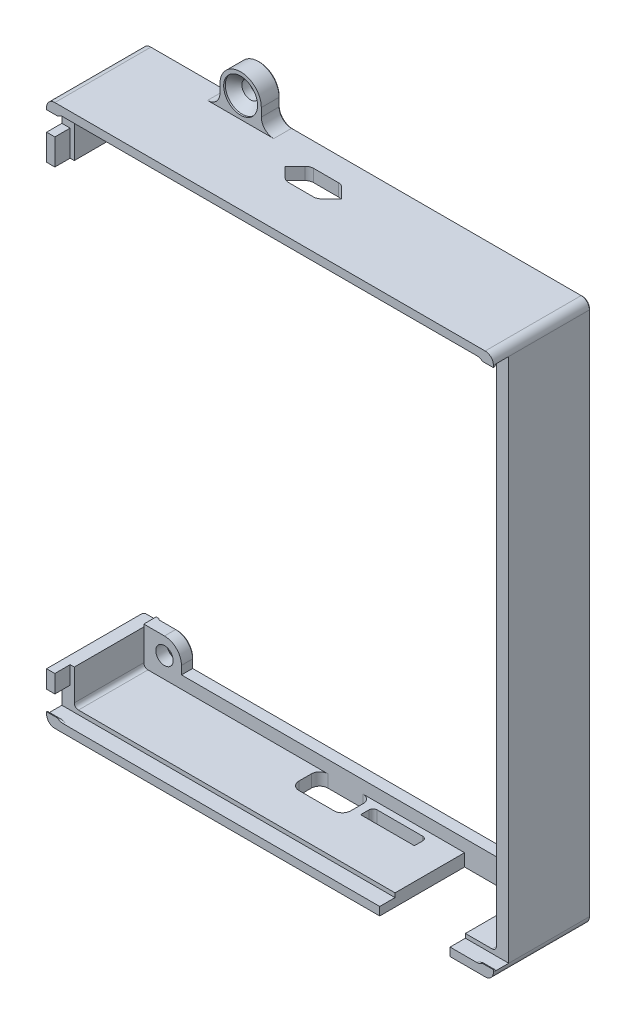
SolidWorks part; units mm, degrees
material "Custom Plastic"
ref_plane "Front Plane" through (0, 0, 0) normal (0, 0, 1) x (1, 0, 0)
ref_plane "Top Plane" through (0, 0, 0) normal (0, 1, 0) x (1, 0, 0)
ref_plane "Right Plane" through (0, 0, 0) normal (1, 0, 0) x (0, 0, -1)
sketch "Model" plane through (0, 0, 0) normal (0, 0, 1) x (1, 0, 0)
  line L0 (104.1673, 32.1811) -> (4.1672, 32.1811)
  line L1 (104.1673, 155.1806) -> (104.1673, 32.1811)
  line L2 (4.1672, 155.1806) -> (104.1673, 155.1806)
  line L3 (4.1672, 32.1811) -> (4.1672, 155.1806)
  line L4 (44.9158, 146.4259) -> (47.4224, 146.4259)
  line L5 (47.4224, 146.4259) -> (47.4224, 148.9326)
  line L6 (47.4224, 148.9326) -> (44.9158, 148.9326)
  line L7 (44.9158, 148.9326) -> (44.9158, 146.4259)
  line L8 (77.4127, 147.4278) -> (79.9193, 147.4278)
  line L9 (79.9193, 147.4278) -> (79.9193, 149.9344)
  line L10 (79.9193, 149.9344) -> (77.4127, 149.9344)
  line L11 (77.4127, 149.9344) -> (77.4127, 147.4278)
  line L12 (6.3266, 141.9721) -> (8.3592, 141.9721)
  line L13 (8.3592, 141.9721) -> (8.3592, 144.0047)
  line L14 (8.3592, 144.0047) -> (6.3266, 144.0047)
  line L15 (6.3266, 144.0047) -> (6.3266, 141.9721)
  line L16 (6.3266, 121.6529) -> (8.3592, 121.6529)
  line L17 (8.3592, 121.6529) -> (8.3592, 123.6855)
  line L18 (8.3592, 123.6855) -> (6.3266, 123.6855)
  line L19 (6.3266, 123.6855) -> (6.3266, 121.6529)
  line L20 (6.3266, 101.3324) -> (8.3592, 101.3324)
  line L21 (8.3592, 101.3324) -> (8.3592, 103.365)
  line L22 (8.3592, 103.365) -> (6.3266, 103.365)
  line L23 (6.3266, 103.365) -> (6.3266, 101.3324)
  line L24 (6.3266, 81.0118) -> (8.3592, 81.0118)
  line L25 (8.3592, 81.0118) -> (8.3592, 83.0444)
  line L26 (8.3592, 83.0444) -> (6.3266, 83.0444)
  line L27 (6.3266, 83.0444) -> (6.3266, 81.0118)
  line L28 (6.3266, 60.6927) -> (8.3592, 60.6927)
  line L29 (8.3592, 60.6927) -> (8.3592, 62.7253)
  line L30 (8.3592, 62.7253) -> (6.3266, 62.7253)
  line L31 (6.3266, 62.7253) -> (6.3266, 60.6927)
  line L32 (85.9221, 148.4144) -> (87.9547, 148.4144)
  line L33 (87.9547, 148.4144) -> (87.9547, 150.447)
  line L34 (87.9547, 150.447) -> (85.9221, 150.447)
  line L35 (85.9221, 150.447) -> (85.9221, 148.4144)
  line L36 (6.3266, 50.5324) -> (8.3592, 50.5324)
  line L37 (8.3592, 50.5324) -> (8.3592, 52.565)
  line L38 (8.3592, 52.565) -> (6.3266, 52.565)
  line L39 (6.3266, 52.565) -> (6.3266, 50.5324)
  line L40 (6.3266, 42.9118) -> (8.3592, 42.9118)
  line L41 (8.3592, 42.9118) -> (8.3592, 44.9444)
  line L42 (8.3592, 44.9444) -> (6.3266, 44.9444)
  line L43 (6.3266, 44.9444) -> (6.3266, 42.9118)
  line L44 (52.8726, 50.0418) -> (54.3815, 50.0418)
  line L45 (54.3815, 50.0418) -> (54.3815, 51.5508)
  line L46 (54.3815, 51.5508) -> (52.8726, 51.5508)
  line L47 (52.8726, 51.5508) -> (52.8726, 50.0418)
  line L48 (58.4219, 130.1637) -> (60.4545, 130.1637)
  line L49 (60.4545, 130.1637) -> (60.4545, 132.1963)
  line L50 (60.4545, 132.1963) -> (58.4219, 132.1963)
  line L51 (58.4219, 132.1963) -> (58.4219, 130.1637)
  line L52 (97.8807, 141.1439) -> (99.9133, 141.1439)
  line L53 (99.9133, 141.1439) -> (99.9133, 143.1765)
  line L54 (99.9133, 143.1765) -> (97.8807, 143.1765)
  line L55 (97.8807, 143.1765) -> (97.8807, 141.1439)
  line L56 (48.438, 37.3046) -> (48.438, 37.0552)
  line L57 (49.9456, 37.0552) -> (49.9456, 37.3046)
  line L58 (52.8877, 37.3046) -> (52.8877, 37.0552)
  line L59 (54.3967, 37.0552) -> (54.3967, 37.3046)
  line L60 (54.3126, 34.0993) -> (54.3126, 33.8995)
  line L61 (56.7201, 33.8995) -> (56.7201, 34.0993)
  line L62 (46.1133, 34.0993) -> (46.1133, 33.8995)
  line L63 (48.5207, 33.8995) -> (48.5207, 34.0993)
  line L64 (82.9607, 49.0165) -> (84.9933, 49.0165)
  line L65 (84.9933, 49.0165) -> (84.9933, 51.0492)
  line L66 (84.9933, 51.0492) -> (82.9607, 51.0492)
  line L67 (82.9607, 51.0492) -> (82.9607, 49.0165)
  line L68 (29.8828, 70.9163) -> (31.9154, 70.9163)
  line L69 (31.9154, 70.9163) -> (31.9154, 72.9489)
  line L70 (31.9154, 72.9489) -> (29.8828, 72.9489)
  line L71 (29.8828, 72.9489) -> (29.8828, 70.9163)
  line L72 (29.8828, 68.1658) -> (31.9154, 68.1658)
  line L73 (31.9154, 68.1658) -> (31.9154, 70.1984)
  line L74 (31.9154, 70.1984) -> (29.8828, 70.1984)
  line L75 (29.8828, 70.1984) -> (29.8828, 68.1658)
  line L76 (29.8828, 108.6649) -> (31.9154, 108.6649)
  line L77 (31.9154, 108.6649) -> (31.9154, 110.6975)
  line L78 (31.9154, 110.6975) -> (29.8828, 110.6975)
  line L79 (29.8828, 110.6975) -> (29.8828, 108.6649)
  line L80 (29.8828, 111.4141) -> (31.9154, 111.4141)
  line L81 (31.9154, 111.4141) -> (31.9154, 113.4467)
  line L82 (31.9154, 113.4467) -> (29.8828, 113.4467)
  line L83 (29.8828, 113.4467) -> (29.8828, 111.4141)
  line L84 (29.8828, 91.1652) -> (31.9154, 91.1652)
  line L85 (31.9154, 91.1652) -> (31.9154, 93.1978)
  line L86 (31.9154, 93.1978) -> (29.8828, 93.1978)
  line L87 (29.8828, 93.1978) -> (29.8828, 91.1652)
  line L88 (29.8828, 88.4147) -> (31.9154, 88.4147)
  line L89 (31.9154, 88.4147) -> (31.9154, 90.4473)
  line L90 (31.9154, 90.4473) -> (29.8828, 90.4473)
  line L91 (29.8828, 90.4473) -> (29.8828, 88.4147)
  line L92 (29.8828, 128.6658) -> (31.9154, 128.6658)
  line L93 (31.9154, 128.6658) -> (31.9154, 130.6984)
  line L94 (31.9154, 130.6984) -> (29.8828, 130.6984)
  line L95 (29.8828, 130.6984) -> (29.8828, 128.6658)
  line L96 (29.8828, 131.4163) -> (31.9154, 131.4163)
  line L97 (31.9154, 131.4163) -> (31.9154, 133.4489)
  line L98 (31.9154, 133.4489) -> (29.8828, 133.4489)
  line L99 (29.8828, 133.4489) -> (29.8828, 131.4163)
  line L100 (48.1611, 135.1453) -> (50.1937, 135.1453)
  line L101 (50.1937, 135.1453) -> (50.1937, 137.1779)
  line L102 (50.1937, 137.1779) -> (48.1611, 137.1779)
  line L103 (48.1611, 137.1779) -> (48.1611, 135.1453)
  line L104 (11.4074, 121.6529) -> (13.44, 121.6529)
  line L105 (13.44, 121.6529) -> (13.44, 123.6855)
  line L106 (13.44, 123.6855) -> (11.4074, 123.6855)
  line L107 (11.4074, 123.6855) -> (11.4074, 121.6529)
  line L108 (104.1673, 32.1811) -> (4.1672, 32.1811)
  line L109 (104.1673, 155.1806) -> (104.1673, 32.1811)
  line L110 (4.1672, 155.1806) -> (104.1673, 155.1806)
  line L111 (4.1672, 32.1811) -> (4.1672, 155.1806)
  spline S0 degree 3 poles (55.1711, 147.6799) (55.1711, 149.685) (52.1643, 149.685) (52.1643, 147.6799) knots 0 0 0 0 1 1 1 1
  spline S1 degree 3 poles (52.1643, 147.6799) (52.1643, 145.6749) (55.1711, 145.6749) (55.1711, 147.6799) knots 0 0 0 0 1 1 1 1
  spline S2 degree 3 poles (75.1706, 148.6804) (75.1706, 150.6854) (72.1637, 150.6854) (72.1637, 148.6804) knots 0 0 0 0 1 1 1 1
  spline S3 degree 3 poles (72.1637, 148.6804) (72.1637, 146.6754) (75.1706, 146.6754) (75.1706, 148.6804) knots 0 0 0 0 1 1 1 1
  spline S4 degree 3 poles (8.3592, 140.448) (8.3592, 141.8026) (6.3266, 141.8026) (6.3266, 140.448) knots 0 0 0 0 1 1 1 1
  spline S5 degree 3 poles (6.3266, 140.448) (6.3266, 139.0934) (8.3592, 139.0934) (8.3592, 140.448) knots 0 0 0 0 1 1 1 1
  spline S6 degree 3 poles (8.3592, 137.9083) (8.3592, 139.2629) (6.3266, 139.2629) (6.3266, 137.9083) knots 0 0 0 0 1 1 1 1
  spline S7 degree 3 poles (6.3266, 137.9083) (6.3266, 136.5537) (8.3592, 136.5537) (8.3592, 137.9083) knots 0 0 0 0 1 1 1 1
  spline S8 degree 3 poles (8.3592, 135.3686) (8.3592, 136.7232) (6.3266, 136.7232) (6.3266, 135.3686) knots 0 0 0 0 1 1 1 1
  spline S9 degree 3 poles (6.3266, 135.3686) (6.3266, 134.0139) (8.3592, 134.0139) (8.3592, 135.3686) knots 0 0 0 0 1 1 1 1
  spline S10 degree 3 poles (8.3592, 132.8288) (8.3592, 134.1834) (6.3266, 134.1834) (6.3266, 132.8288) knots 0 0 0 0 1 1 1 1
  spline S11 degree 3 poles (6.3266, 132.8288) (6.3266, 131.4742) (8.3592, 131.4742) (8.3592, 132.8288) knots 0 0 0 0 1 1 1 1
  spline S12 degree 3 poles (8.3592, 130.2891) (8.3592, 131.6437) (6.3266, 131.6437) (6.3266, 130.2891) knots 0 0 0 0 1 1 1 1
  spline S13 degree 3 poles (6.3266, 130.2891) (6.3266, 128.9331) (8.3592, 128.9331) (8.3592, 130.2891) knots 0 0 0 0 1 1 1 1
  spline S14 degree 3 poles (8.3592, 127.748) (8.3592, 129.1026) (6.3266, 129.1026) (6.3266, 127.748) knots 0 0 0 0 1 1 1 1
  spline S15 degree 3 poles (6.3266, 127.748) (6.3266, 126.3934) (8.3592, 126.3934) (8.3592, 127.748) knots 0 0 0 0 1 1 1 1
  spline S16 degree 3 poles (8.3592, 120.1288) (8.3592, 121.4834) (6.3266, 121.4834) (6.3266, 120.1288) knots 0 0 0 0 1 1 1 1
  spline S17 degree 3 poles (6.3266, 120.1288) (6.3266, 118.7742) (8.3592, 118.7742) (8.3592, 120.1288) knots 0 0 0 0 1 1 1 1
  spline S18 degree 3 poles (8.3592, 117.5891) (8.3592, 118.9437) (6.3266, 118.9437) (6.3266, 117.5891) knots 0 0 0 0 1 1 1 1
  spline S19 degree 3 poles (6.3266, 117.5891) (6.3266, 116.2331) (8.3592, 116.2331) (8.3592, 117.5891) knots 0 0 0 0 1 1 1 1
  spline S20 degree 3 poles (8.3592, 115.048) (8.3592, 116.4026) (6.3266, 116.4026) (6.3266, 115.048) knots 0 0 0 0 1 1 1 1
  spline S21 degree 3 poles (6.3266, 115.048) (6.3266, 113.6934) (8.3592, 113.6934) (8.3592, 115.048) knots 0 0 0 0 1 1 1 1
  spline S22 degree 3 poles (8.3592, 112.5083) (8.3592, 113.8629) (6.3266, 113.8629) (6.3266, 112.5083) knots 0 0 0 0 1 1 1 1
  spline S23 degree 3 poles (6.3266, 112.5083) (6.3266, 111.1537) (8.3592, 111.1537) (8.3592, 112.5083) knots 0 0 0 0 1 1 1 1
  spline S24 degree 3 poles (8.3592, 109.9686) (8.3592, 111.3232) (6.3266, 111.3232) (6.3266, 109.9686) knots 0 0 0 0 1 1 1 1
  spline S25 degree 3 poles (6.3266, 109.9686) (6.3266, 108.6139) (8.3592, 108.6139) (8.3592, 109.9686) knots 0 0 0 0 1 1 1 1
  spline S26 degree 3 poles (8.3592, 107.4288) (8.3592, 108.7834) (6.3266, 108.7834) (6.3266, 107.4288) knots 0 0 0 0 1 1 1 1
  spline S27 degree 3 poles (6.3266, 107.4288) (6.3266, 106.0742) (8.3592, 106.0742) (8.3592, 107.4288) knots 0 0 0 0 1 1 1 1
  spline S28 degree 3 poles (8.3592, 99.8083) (8.3592, 101.1629) (6.3266, 101.1629) (6.3266, 99.8083) knots 0 0 0 0 1 1 1 1
  spline S29 degree 3 poles (6.3266, 99.8083) (6.3266, 98.4537) (8.3592, 98.4537) (8.3592, 99.8083) knots 0 0 0 0 1 1 1 1
  spline S30 degree 3 poles (8.3592, 97.2686) (8.3592, 98.6232) (6.3266, 98.6232) (6.3266, 97.2686) knots 0 0 0 0 1 1 1 1
  spline S31 degree 3 poles (6.3266, 97.2686) (6.3266, 95.9139) (8.3592, 95.9139) (8.3592, 97.2686) knots 0 0 0 0 1 1 1 1
  spline S32 degree 3 poles (8.3592, 94.7288) (8.3592, 96.0834) (6.3266, 96.0834) (6.3266, 94.7288) knots 0 0 0 0 1 1 1 1
  spline S33 degree 3 poles (6.3266, 94.7288) (6.3266, 93.3742) (8.3592, 93.3742) (8.3592, 94.7288) knots 0 0 0 0 1 1 1 1
  spline S34 degree 3 poles (8.3592, 92.1891) (8.3592, 93.5437) (6.3266, 93.5437) (6.3266, 92.1891) knots 0 0 0 0 1 1 1 1
  spline S35 degree 3 poles (6.3266, 92.1891) (6.3266, 90.8331) (8.3592, 90.8331) (8.3592, 92.1891) knots 0 0 0 0 1 1 1 1
  spline S36 degree 3 poles (8.3592, 89.648) (8.3592, 91.0026) (6.3266, 91.0026) (6.3266, 89.648) knots 0 0 0 0 1 1 1 1
  spline S37 degree 3 poles (6.3266, 89.648) (6.3266, 88.2934) (8.3592, 88.2934) (8.3592, 89.648) knots 0 0 0 0 1 1 1 1
  spline S38 degree 3 poles (8.3592, 87.1083) (8.3592, 88.4629) (6.3266, 88.4629) (6.3266, 87.1083) knots 0 0 0 0 1 1 1 1
  spline S39 degree 3 poles (6.3266, 87.1083) (6.3266, 85.7537) (8.3592, 85.7537) (8.3592, 87.1083) knots 0 0 0 0 1 1 1 1
  spline S40 degree 3 poles (8.3592, 79.4891) (8.3592, 80.8437) (6.3266, 80.8437) (6.3266, 79.4891) knots 0 0 0 0 1 1 1 1
  spline S41 degree 3 poles (6.3266, 79.4891) (6.3266, 78.1331) (8.3592, 78.1331) (8.3592, 79.4891) knots 0 0 0 0 1 1 1 1
  spline S42 degree 3 poles (8.3592, 76.948) (8.3592, 78.3026) (6.3266, 78.3026) (6.3266, 76.948) knots 0 0 0 0 1 1 1 1
  spline S43 degree 3 poles (6.3266, 76.948) (6.3266, 75.5934) (8.3592, 75.5934) (8.3592, 76.948) knots 0 0 0 0 1 1 1 1
  spline S44 degree 3 poles (8.3592, 74.4083) (8.3592, 75.7629) (6.3266, 75.7629) (6.3266, 74.4083) knots 0 0 0 0 1 1 1 1
  spline S45 degree 3 poles (6.3266, 74.4083) (6.3266, 73.0537) (8.3592, 73.0537) (8.3592, 74.4083) knots 0 0 0 0 1 1 1 1
  spline S46 degree 3 poles (8.3592, 71.8685) (8.3592, 73.2232) (6.3266, 73.2232) (6.3266, 71.8685) knots 0 0 0 0 1 1 1 1
  spline S47 degree 3 poles (6.3266, 71.8685) (6.3266, 70.5139) (8.3592, 70.5139) (8.3592, 71.8685) knots 0 0 0 0 1 1 1 1
  spline S48 degree 3 poles (8.3592, 69.3288) (8.3592, 70.6834) (6.3266, 70.6834) (6.3266, 69.3288) knots 0 0 0 0 1 1 1 1
  spline S49 degree 3 poles (6.3266, 69.3288) (6.3266, 67.9742) (8.3592, 67.9742) (8.3592, 69.3288) knots 0 0 0 0 1 1 1 1
  spline S50 degree 3 poles (8.3592, 66.7891) (8.3592, 68.1437) (6.3266, 68.1437) (6.3266, 66.7891) knots 0 0 0 0 1 1 1 1
  spline S51 degree 3 poles (6.3266, 66.7891) (6.3266, 65.4331) (8.3592, 65.4331) (8.3592, 66.7891) knots 0 0 0 0 1 1 1 1
  spline S52 degree 3 poles (8.3592, 59.1686) (8.3592, 60.5232) (6.3266, 60.5232) (6.3266, 59.1686) knots 0 0 0 0 1 1 1 1
  spline S53 degree 3 poles (6.3266, 59.1686) (6.3266, 57.8139) (8.3592, 57.8139) (8.3592, 59.1686) knots 0 0 0 0 1 1 1 1
  spline S54 degree 3 poles (8.3592, 56.6288) (8.3592, 57.9834) (6.3266, 57.9834) (6.3266, 56.6288) knots 0 0 0 0 1 1 1 1
  spline S55 degree 3 poles (6.3266, 56.6288) (6.3266, 55.2742) (8.3592, 55.2742) (8.3592, 56.6288) knots 0 0 0 0 1 1 1 1
  spline S56 degree 3 poles (8.3592, 54.0891) (8.3592, 55.4437) (6.3266, 55.4437) (6.3266, 54.0891) knots 0 0 0 0 1 1 1 1
  spline S57 degree 3 poles (6.3266, 54.0891) (6.3266, 52.7331) (8.3592, 52.7331) (8.3592, 54.0891) knots 0 0 0 0 1 1 1 1
  spline S58 degree 3 poles (85.4149, 149.4301) (85.4149, 150.7847) (83.3823, 150.7847) (83.3823, 149.4301) knots 0 0 0 0 1 1 1 1
  spline S59 degree 3 poles (83.3823, 149.4301) (83.3823, 148.0754) (85.4149, 148.0754) (85.4149, 149.4301) knots 0 0 0 0 1 1 1 1
  spline S60 degree 3 poles (8.3592, 49.0083) (8.3592, 50.3629) (6.3266, 50.3629) (6.3266, 49.0083) knots 0 0 0 0 1 1 1 1
  spline S61 degree 3 poles (6.3266, 49.0083) (6.3266, 47.6537) (8.3592, 47.6537) (8.3592, 49.0083) knots 0 0 0 0 1 1 1 1
  spline S62 degree 3 poles (8.3592, 41.3891) (8.3592, 42.7437) (6.3266, 42.7437) (6.3266, 41.3891) knots 0 0 0 0 1 1 1 1
  spline S63 degree 3 poles (6.3266, 41.3891) (6.3266, 40.0331) (8.3592, 40.0331) (8.3592, 41.3891) knots 0 0 0 0 1 1 1 1
  spline S64 degree 3 poles (54.3815, 52.0661) (54.3815, 53.0721) (52.8726, 53.0721) (52.8726, 52.0661) knots 0 0 0 0 1 1 1 1
  spline S65 degree 3 poles (52.8726, 52.0661) (52.8726, 51.0602) (54.3815, 51.0602) (54.3815, 52.0661) knots 0 0 0 0 1 1 1 1
  spline S66 degree 3 poles (55.6507, 50.797) (55.6507, 51.8029) (54.1417, 51.8029) (54.1417, 50.797) knots 0 0 0 0 1 1 1 1
  spline S67 degree 3 poles (54.1417, 50.797) (54.1417, 49.791) (55.6507, 49.791) (55.6507, 50.797) knots 0 0 0 0 1 1 1 1
  spline S68 degree 3 poles (55.6507, 52.0661) (55.6507, 53.0721) (54.1417, 53.0721) (54.1417, 52.0661) knots 0 0 0 0 1 1 1 1
  spline S69 degree 3 poles (54.1417, 52.0661) (54.1417, 51.0602) (55.6507, 51.0602) (55.6507, 52.0661) knots 0 0 0 0 1 1 1 1
  spline S70 degree 3 poles (56.9212, 50.797) (56.9212, 51.8029) (55.4123, 51.8029) (55.4123, 50.797) knots 0 0 0 0 1 1 1 1
  spline S71 degree 3 poles (55.4123, 50.797) (55.4123, 49.791) (56.9212, 49.791) (56.9212, 50.797) knots 0 0 0 0 1 1 1 1
  spline S72 degree 3 poles (56.9212, 52.0661) (56.9212, 53.0721) (55.4123, 53.0721) (55.4123, 52.0661) knots 0 0 0 0 1 1 1 1
  spline S73 degree 3 poles (55.4123, 52.0661) (55.4123, 51.0602) (56.9212, 51.0602) (56.9212, 52.0661) knots 0 0 0 0 1 1 1 1
  spline S74 degree 3 poles (58.1904, 50.797) (58.1904, 51.8029) (56.6828, 51.8029) (56.6828, 50.797) knots 0 0 0 0 1 1 1 1
  spline S75 degree 3 poles (56.6828, 50.797) (56.6828, 49.791) (58.1904, 49.791) (58.1904, 50.797) knots 0 0 0 0 1 1 1 1
  spline S76 degree 3 poles (58.1904, 52.0661) (58.1904, 53.0721) (56.6828, 53.0721) (56.6828, 52.0661) knots 0 0 0 0 1 1 1 1
  spline S77 degree 3 poles (56.6828, 52.0661) (56.6828, 51.0602) (58.1904, 51.0602) (58.1904, 52.0661) knots 0 0 0 0 1 1 1 1
  spline S78 degree 3 poles (59.461, 50.797) (59.461, 51.8029) (57.952, 51.8029) (57.952, 50.797) knots 0 0 0 0 1 1 1 1
  spline S79 degree 3 poles (57.952, 50.797) (57.952, 49.791) (59.461, 49.791) (59.461, 50.797) knots 0 0 0 0 1 1 1 1
  spline S80 degree 3 poles (59.461, 52.0661) (59.461, 53.0721) (57.952, 53.0721) (57.952, 52.0661) knots 0 0 0 0 1 1 1 1
  spline S81 degree 3 poles (57.952, 52.0661) (57.952, 51.0602) (59.461, 51.0602) (59.461, 52.0661) knots 0 0 0 0 1 1 1 1
  spline S82 degree 3 poles (57.9148, 131.1793) (57.9148, 132.5353) (55.8822, 132.5353) (55.8822, 131.1793) knots 0 0 0 0 1 1 1 1
  spline S83 degree 3 poles (55.8822, 131.1793) (55.8822, 129.8247) (57.9148, 129.8247) (57.9148, 131.1793) knots 0 0 0 0 1 1 1 1
  spline S84 degree 3 poles (63.2437, 36.9311) (63.2437, 37.9371) (61.7347, 37.9371) (61.7347, 36.9311) knots 0 0 0 0 1 1 1 1
  spline S85 degree 3 poles (61.7347, 36.9311) (61.7347, 35.9252) (63.2437, 35.9252) (63.2437, 36.9311) knots 0 0 0 0 1 1 1 1
  spline S86 degree 3 poles (71.2239, 36.9311) (71.2239, 37.9371) (69.715, 37.9371) (69.715, 36.9311) knots 0 0 0 0 1 1 1 1
  spline S87 degree 3 poles (69.715, 36.9311) (69.715, 35.9252) (71.2239, 35.9252) (71.2239, 36.9311) knots 0 0 0 0 1 1 1 1
  spline S88 degree 3 poles (102.453, 142.1609) (102.453, 143.5155) (100.4204, 143.5155) (100.4204, 142.1609) knots 0 0 0 0 1 1 1 1
  spline S89 degree 3 poles (100.4204, 142.1609) (100.4204, 140.8063) (102.453, 140.8063) (102.453, 142.1609) knots 0 0 0 0 1 1 1 1
  spline S90 degree 3 poles (99.9133, 129.4609) (99.9133, 130.8155) (97.8807, 130.8155) (97.8807, 129.4609) knots 0 0 0 0 1 1 1 1
  spline S91 degree 3 poles (97.8807, 129.4609) (97.8807, 128.1063) (99.9133, 128.1063) (99.9133, 129.4609) knots 0 0 0 0 1 1 1 1
  spline S92 degree 3 poles (102.453, 139.6198) (102.453, 140.9744) (100.4204, 140.9744) (100.4204, 139.6198) knots 0 0 0 0 1 1 1 1
  spline S93 degree 3 poles (100.4204, 139.6198) (100.4204, 138.2652) (102.453, 138.2652) (102.453, 139.6198) knots 0 0 0 0 1 1 1 1
  spline S94 degree 3 poles (99.9133, 126.9198) (99.9133, 128.2744) (97.8807, 128.2744) (97.8807, 126.9198) knots 0 0 0 0 1 1 1 1
  spline S95 degree 3 poles (97.8807, 126.9198) (97.8807, 125.5652) (99.9133, 125.5652) (99.9133, 126.9198) knots 0 0 0 0 1 1 1 1
  spline S96 degree 3 poles (102.453, 137.0801) (102.453, 138.4347) (100.4204, 138.4347) (100.4204, 137.0801) knots 0 0 0 0 1 1 1 1
  spline S97 degree 3 poles (100.4204, 137.0801) (100.4204, 135.7255) (102.453, 135.7255) (102.453, 137.0801) knots 0 0 0 0 1 1 1 1
  spline S98 degree 3 poles (99.9133, 124.3801) (99.9133, 125.7347) (97.8807, 125.7347) (97.8807, 124.3801) knots 0 0 0 0 1 1 1 1
  spline S99 degree 3 poles (97.8807, 124.3801) (97.8807, 123.0255) (99.9133, 123.0255) (99.9133, 124.3801) knots 0 0 0 0 1 1 1 1
  spline S100 degree 3 poles (102.453, 134.5403) (102.453, 135.895) (100.4204, 135.895) (100.4204, 134.5403) knots 0 0 0 0 1 1 1 1
  spline S101 degree 3 poles (100.4204, 134.5403) (100.4204, 133.1857) (102.453, 133.1857) (102.453, 134.5403) knots 0 0 0 0 1 1 1 1
  spline S102 degree 3 poles (99.9133, 121.8404) (99.9133, 123.195) (97.8807, 123.195) (97.8807, 121.8404) knots 0 0 0 0 1 1 1 1
  spline S103 degree 3 poles (97.8807, 121.8404) (97.8807, 120.4857) (99.9133, 120.4857) (99.9133, 121.8404) knots 0 0 0 0 1 1 1 1
  spline S104 degree 3 poles (102.453, 132.0006) (102.453, 133.3552) (100.4204, 133.3552) (100.4204, 132.0006) knots 0 0 0 0 1 1 1 1
  spline S105 degree 3 poles (100.4204, 132.0006) (100.4204, 130.646) (102.453, 130.646) (102.453, 132.0006) knots 0 0 0 0 1 1 1 1
  spline S106 degree 3 poles (99.9133, 119.3006) (99.9133, 120.6552) (97.8807, 120.6552) (97.8807, 119.3006) knots 0 0 0 0 1 1 1 1
  spline S107 degree 3 poles (97.8807, 119.3006) (97.8807, 117.946) (99.9133, 117.946) (99.9133, 119.3006) knots 0 0 0 0 1 1 1 1
  spline S108 degree 3 poles (102.453, 129.4609) (102.453, 130.8155) (100.4204, 130.8155) (100.4204, 129.4609) knots 0 0 0 0 1 1 1 1
  spline S109 degree 3 poles (100.4204, 129.4609) (100.4204, 128.1063) (102.453, 128.1063) (102.453, 129.4609) knots 0 0 0 0 1 1 1 1
  spline S110 degree 3 poles (99.9133, 116.7609) (99.9133, 118.1155) (97.8807, 118.1155) (97.8807, 116.7609) knots 0 0 0 0 1 1 1 1
  spline S111 degree 3 poles (97.8807, 116.7609) (97.8807, 115.4063) (99.9133, 115.4063) (99.9133, 116.7609) knots 0 0 0 0 1 1 1 1
  spline S112 degree 3 poles (102.453, 126.9198) (102.453, 128.2744) (100.4204, 128.2744) (100.4204, 126.9198) knots 0 0 0 0 1 1 1 1
  spline S113 degree 3 poles (100.4204, 126.9198) (100.4204, 125.5652) (102.453, 125.5652) (102.453, 126.9198) knots 0 0 0 0 1 1 1 1
  spline S114 degree 3 poles (99.9133, 114.2198) (99.9133, 115.5744) (97.8807, 115.5744) (97.8807, 114.2198) knots 0 0 0 0 1 1 1 1
  spline S115 degree 3 poles (97.8807, 114.2198) (97.8807, 112.8652) (99.9133, 112.8652) (99.9133, 114.2198) knots 0 0 0 0 1 1 1 1
  spline S116 degree 3 poles (102.453, 124.3801) (102.453, 125.7347) (100.4204, 125.7347) (100.4204, 124.3801) knots 0 0 0 0 1 1 1 1
  spline S117 degree 3 poles (100.4204, 124.3801) (100.4204, 123.0255) (102.453, 123.0255) (102.453, 124.3801) knots 0 0 0 0 1 1 1 1
  spline S118 degree 3 poles (99.9133, 111.6801) (99.9133, 113.0347) (97.8807, 113.0347) (97.8807, 111.6801) knots 0 0 0 0 1 1 1 1
  spline S119 degree 3 poles (97.8807, 111.6801) (97.8807, 110.3255) (99.9133, 110.3255) (99.9133, 111.6801) knots 0 0 0 0 1 1 1 1
  spline S120 degree 3 poles (102.453, 121.8404) (102.453, 123.195) (100.4204, 123.195) (100.4204, 121.8404) knots 0 0 0 0 1 1 1 1
  spline S121 degree 3 poles (100.4204, 121.8404) (100.4204, 120.4857) (102.453, 120.4857) (102.453, 121.8404) knots 0 0 0 0 1 1 1 1
  spline S122 degree 3 poles (99.9133, 109.1404) (99.9133, 110.495) (97.8807, 110.495) (97.8807, 109.1404) knots 0 0 0 0 1 1 1 1
  spline S123 degree 3 poles (97.8807, 109.1404) (97.8807, 107.7857) (99.9133, 107.7857) (99.9133, 109.1404) knots 0 0 0 0 1 1 1 1
  spline S124 degree 3 poles (102.453, 119.3006) (102.453, 120.6552) (100.4204, 120.6552) (100.4204, 119.3006) knots 0 0 0 0 1 1 1 1
  spline S125 degree 3 poles (100.4204, 119.3006) (100.4204, 117.946) (102.453, 117.946) (102.453, 119.3006) knots 0 0 0 0 1 1 1 1
  spline S126 degree 3 poles (99.9133, 106.6006) (99.9133, 107.9552) (97.8807, 107.9552) (97.8807, 106.6006) knots 0 0 0 0 1 1 1 1
  spline S127 degree 3 poles (97.8807, 106.6006) (97.8807, 105.246) (99.9133, 105.246) (99.9133, 106.6006) knots 0 0 0 0 1 1 1 1
  spline S128 degree 3 poles (102.453, 116.7609) (102.453, 118.1155) (100.4204, 118.1155) (100.4204, 116.7609) knots 0 0 0 0 1 1 1 1
  spline S129 degree 3 poles (100.4204, 116.7609) (100.4204, 115.4063) (102.453, 115.4063) (102.453, 116.7609) knots 0 0 0 0 1 1 1 1
  spline S130 degree 3 poles (99.9133, 104.0609) (99.9133, 105.4155) (97.8807, 105.4155) (97.8807, 104.0609) knots 0 0 0 0 1 1 1 1
  spline S131 degree 3 poles (97.8807, 104.0609) (97.8807, 102.7063) (99.9133, 102.7063) (99.9133, 104.0609) knots 0 0 0 0 1 1 1 1
  spline S132 degree 3 poles (102.453, 114.2198) (102.453, 115.5744) (100.4204, 115.5744) (100.4204, 114.2198) knots 0 0 0 0 1 1 1 1
  spline S133 degree 3 poles (100.4204, 114.2198) (100.4204, 112.8652) (102.453, 112.8652) (102.453, 114.2198) knots 0 0 0 0 1 1 1 1
  spline S134 degree 3 poles (102.453, 111.6801) (102.453, 113.0347) (100.4204, 113.0347) (100.4204, 111.6801) knots 0 0 0 0 1 1 1 1
  spline S135 degree 3 poles (100.4204, 111.6801) (100.4204, 110.3255) (102.453, 110.3255) (102.453, 111.6801) knots 0 0 0 0 1 1 1 1
  spline S136 degree 3 poles (99.9133, 101.5198) (99.9133, 102.8744) (97.8807, 102.8744) (97.8807, 101.5198) knots 0 0 0 0 1 1 1 1
  spline S137 degree 3 poles (97.8807, 101.5198) (97.8807, 100.1652) (99.9133, 100.1652) (99.9133, 101.5198) knots 0 0 0 0 1 1 1 1
  spline S138 degree 3 poles (102.453, 109.1404) (102.453, 110.495) (100.4204, 110.495) (100.4204, 109.1404) knots 0 0 0 0 1 1 1 1
  spline S139 degree 3 poles (100.4204, 109.1404) (100.4204, 107.7857) (102.453, 107.7857) (102.453, 109.1404) knots 0 0 0 0 1 1 1 1
  spline S140 degree 3 poles (102.453, 104.0609) (102.453, 105.4155) (100.4204, 105.4155) (100.4204, 104.0609) knots 0 0 0 0 1 1 1 1
  spline S141 degree 3 poles (100.4204, 104.0609) (100.4204, 102.7063) (102.453, 102.7063) (102.453, 104.0609) knots 0 0 0 0 1 1 1 1
  spline S142 degree 3 poles (102.453, 101.5198) (102.453, 102.8744) (100.4204, 102.8744) (100.4204, 101.5198) knots 0 0 0 0 1 1 1 1
  spline S143 degree 3 poles (100.4204, 101.5198) (100.4204, 100.1652) (102.453, 100.1652) (102.453, 101.5198) knots 0 0 0 0 1 1 1 1
  spline S144 degree 3 poles (102.453, 98.9801) (102.453, 100.3347) (100.4204, 100.3347) (100.4204, 98.9801) knots 0 0 0 0 1 1 1 1
  spline S145 degree 3 poles (100.4204, 98.9801) (100.4204, 97.6255) (102.453, 97.6255) (102.453, 98.9801) knots 0 0 0 0 1 1 1 1
  spline S146 degree 3 poles (102.453, 96.4404) (102.453, 97.795) (100.4204, 97.795) (100.4204, 96.4404) knots 0 0 0 0 1 1 1 1
  spline S147 degree 3 poles (100.4204, 96.4404) (100.4204, 95.0857) (102.453, 95.0857) (102.453, 96.4404) knots 0 0 0 0 1 1 1 1
  spline S148 degree 3 poles (99.9133, 98.9801) (99.9133, 100.3347) (97.8807, 100.3347) (97.8807, 98.9801) knots 0 0 0 0 1 1 1 1
  spline S149 degree 3 poles (97.8807, 98.9801) (97.8807, 97.6255) (99.9133, 97.6255) (99.9133, 98.9801) knots 0 0 0 0 1 1 1 1
  spline S150 degree 3 poles (99.9133, 96.4404) (99.9133, 97.795) (97.8807, 97.795) (97.8807, 96.4404) knots 0 0 0 0 1 1 1 1
  spline S151 degree 3 poles (97.8807, 96.4404) (97.8807, 95.0857) (99.9133, 95.0857) (99.9133, 96.4404) knots 0 0 0 0 1 1 1 1
  spline S152 degree 3 poles (99.9133, 139.6198) (99.9133, 140.9744) (97.8807, 140.9744) (97.8807, 139.6198) knots 0 0 0 0 1 1 1 1
  spline S153 degree 3 poles (97.8807, 139.6198) (97.8807, 138.2652) (99.9133, 138.2652) (99.9133, 139.6198) knots 0 0 0 0 1 1 1 1
  spline S154 degree 3 poles (99.9133, 137.0801) (99.9133, 138.4347) (97.8807, 138.4347) (97.8807, 137.0801) knots 0 0 0 0 1 1 1 1
  spline S155 degree 3 poles (97.8807, 137.0801) (97.8807, 135.7255) (99.9133, 135.7255) (99.9133, 137.0801) knots 0 0 0 0 1 1 1 1
  spline S156 degree 3 poles (99.9133, 134.5403) (99.9133, 135.895) (97.8807, 135.895) (97.8807, 134.5403) knots 0 0 0 0 1 1 1 1
  spline S157 degree 3 poles (97.8807, 134.5403) (97.8807, 133.1857) (99.9133, 133.1857) (99.9133, 134.5403) knots 0 0 0 0 1 1 1 1
  spline S158 degree 3 poles (99.9133, 132.0006) (99.9133, 133.3552) (97.8807, 133.3552) (97.8807, 132.0006) knots 0 0 0 0 1 1 1 1
  spline S159 degree 3 poles (97.8807, 132.0006) (97.8807, 130.646) (99.9133, 130.646) (99.9133, 132.0006) knots 0 0 0 0 1 1 1 1
  spline S160 degree 3 poles (99.9133, 93.9006) (99.9133, 95.2552) (97.8807, 95.2552) (97.8807, 93.9006) knots 0 0 0 0 1 1 1 1
  spline S161 degree 3 poles (97.8807, 93.9006) (97.8807, 92.546) (99.9133, 92.546) (99.9133, 93.9006) knots 0 0 0 0 1 1 1 1
  spline S162 degree 3 poles (102.453, 93.9006) (102.453, 95.2552) (100.4204, 95.2552) (100.4204, 93.9006) knots 0 0 0 0 1 1 1 1
  spline S163 degree 3 poles (100.4204, 93.9006) (100.4204, 92.546) (102.453, 92.546) (102.453, 93.9006) knots 0 0 0 0 1 1 1 1
  spline S164 degree 3 poles (102.453, 106.6006) (102.453, 107.9552) (100.4204, 107.9552) (100.4204, 106.6006) knots 0 0 0 0 1 1 1 1
  spline S165 degree 3 poles (100.4204, 106.6006) (100.4204, 105.246) (102.453, 105.246) (102.453, 106.6006) knots 0 0 0 0 1 1 1 1
  spline S166 degree 3 poles (99.9133, 91.3609) (99.9133, 92.7155) (97.8807, 92.7155) (97.8807, 91.3609) knots 0 0 0 0 1 1 1 1
  spline S167 degree 3 poles (97.8807, 91.3609) (97.8807, 90.0063) (99.9133, 90.0063) (99.9133, 91.3609) knots 0 0 0 0 1 1 1 1
  spline S168 degree 3 poles (102.453, 91.3609) (102.453, 92.7155) (100.4204, 92.7155) (100.4204, 91.3609) knots 0 0 0 0 1 1 1 1
  spline S169 degree 3 poles (100.4204, 91.3609) (100.4204, 90.0063) (102.453, 90.0063) (102.453, 91.3609) knots 0 0 0 0 1 1 1 1
  spline S170 degree 3 poles (99.9133, 88.8198) (99.9133, 90.1744) (97.8807, 90.1744) (97.8807, 88.8198) knots 0 0 0 0 1 1 1 1
  spline S171 degree 3 poles (97.8807, 88.8198) (97.8807, 87.4652) (99.9133, 87.4652) (99.9133, 88.8198) knots 0 0 0 0 1 1 1 1
  spline S172 degree 3 poles (102.453, 88.8198) (102.453, 90.1744) (100.4204, 90.1744) (100.4204, 88.8198) knots 0 0 0 0 1 1 1 1
  spline S173 degree 3 poles (100.4204, 88.8198) (100.4204, 87.4652) (102.453, 87.4652) (102.453, 88.8198) knots 0 0 0 0 1 1 1 1
  spline S174 degree 3 poles (99.9133, 86.2801) (99.9133, 87.6347) (97.8807, 87.6347) (97.8807, 86.2801) knots 0 0 0 0 1 1 1 1
  spline S175 degree 3 poles (97.8807, 86.2801) (97.8807, 84.9255) (99.9133, 84.9255) (99.9133, 86.2801) knots 0 0 0 0 1 1 1 1
  spline S176 degree 3 poles (102.453, 86.2801) (102.453, 87.6347) (100.4204, 87.6347) (100.4204, 86.2801) knots 0 0 0 0 1 1 1 1
  spline S177 degree 3 poles (100.4204, 86.2801) (100.4204, 84.9255) (102.453, 84.9255) (102.453, 86.2801) knots 0 0 0 0 1 1 1 1
  spline S178 degree 3 poles (99.9133, 83.7404) (99.9133, 85.095) (97.8807, 85.095) (97.8807, 83.7404) knots 0 0 0 0 1 1 1 1
  spline S179 degree 3 poles (97.8807, 83.7404) (97.8807, 82.3857) (99.9133, 82.3857) (99.9133, 83.7404) knots 0 0 0 0 1 1 1 1
  spline S180 degree 3 poles (102.453, 83.7404) (102.453, 85.095) (100.4204, 85.095) (100.4204, 83.7404) knots 0 0 0 0 1 1 1 1
  spline S181 degree 3 poles (100.4204, 83.7404) (100.4204, 82.3857) (102.453, 82.3857) (102.453, 83.7404) knots 0 0 0 0 1 1 1 1
  spline S182 degree 3 poles (99.9133, 81.2006) (99.9133, 82.5552) (97.8807, 82.5552) (97.8807, 81.2006) knots 0 0 0 0 1 1 1 1
  spline S183 degree 3 poles (97.8807, 81.2006) (97.8807, 79.846) (99.9133, 79.846) (99.9133, 81.2006) knots 0 0 0 0 1 1 1 1
  spline S184 degree 3 poles (102.453, 81.2006) (102.453, 82.5552) (100.4204, 82.5552) (100.4204, 81.2006) knots 0 0 0 0 1 1 1 1
  spline S185 degree 3 poles (100.4204, 81.2006) (100.4204, 79.846) (102.453, 79.846) (102.453, 81.2006) knots 0 0 0 0 1 1 1 1
  spline S186 degree 3 poles (49.9456, 37.3046) (49.9456, 38.3106) (48.438, 38.3106) (48.438, 37.3046) knots 0 0 0 0 1 1 1 1
  spline S187 degree 3 poles (48.438, 37.0552) (48.438, 36.0492) (49.9456, 36.0492) (49.9456, 37.0552) knots 0 0 0 0 1 1 1 1
  spline S188 degree 3 poles (54.3967, 37.3046) (54.3967, 38.3106) (52.8877, 38.3106) (52.8877, 37.3046) knots 0 0 0 0 1 1 1 1
  spline S189 degree 3 poles (52.8877, 37.0552) (52.8877, 36.0492) (54.3967, 36.0492) (54.3967, 37.0552) knots 0 0 0 0 1 1 1 1
  spline S190 degree 3 poles (56.7201, 34.0993) (56.7201, 35.7047) (54.3126, 35.7047) (54.3126, 34.0993) knots 0 0 0 0 1 1 1 1
  spline S191 degree 3 poles (54.3126, 33.8995) (54.3126, 32.2941) (56.7201, 32.2941) (56.7201, 33.8995) knots 0 0 0 0 1 1 1 1
  spline S192 degree 3 poles (48.5207, 34.0993) (48.5207, 35.7047) (46.1133, 35.7047) (46.1133, 34.0993) knots 0 0 0 0 1 1 1 1
  spline S193 degree 3 poles (46.1133, 33.8995) (46.1133, 32.2941) (48.5207, 32.2941) (48.5207, 33.8995) knots 0 0 0 0 1 1 1 1
  spline S194 degree 3 poles (54.4711, 34.0001) (54.4711, 34.9054) (53.1123, 34.9054) (53.1123, 34.0001) knots 0 0 0 0 1 1 1 1
  spline S195 degree 3 poles (53.1123, 34.0001) (53.1123, 33.0933) (54.4711, 33.0933) (54.4711, 34.0001) knots 0 0 0 0 1 1 1 1
  spline S196 degree 3 poles (49.721, 34.0001) (49.721, 34.9054) (48.3623, 34.9054) (48.3623, 34.0001) knots 0 0 0 0 1 1 1 1
  spline S197 degree 3 poles (48.3623, 34.0001) (48.3623, 33.0933) (49.721, 33.0933) (49.721, 34.0001) knots 0 0 0 0 1 1 1 1
  spline S198 degree 3 poles (84.606, 43.6822) (84.606, 46.2205) (80.7985, 46.2205) (80.7985, 43.6822) knots 0 0 0 0 1 1 1 1
  spline S199 degree 3 poles (80.7985, 43.6822) (80.7985, 41.1438) (84.606, 41.1438) (84.606, 43.6822) knots 0 0 0 0 1 1 1 1
  spline S200 degree 3 poles (96.0355, 43.6822) (96.0355, 46.2205) (92.228, 46.2205) (92.228, 43.6822) knots 0 0 0 0 1 1 1 1
  spline S201 degree 3 poles (92.228, 43.6822) (92.228, 41.1438) (96.0355, 41.1438) (96.0355, 43.6822) knots 0 0 0 0 1 1 1 1
  spline S202 degree 3 poles (93.8775, 52.5719) (93.8775, 53.9265) (91.8462, 53.9265) (91.8462, 52.5719) knots 0 0 0 0 1 1 1 1
  spline S203 degree 3 poles (91.8462, 52.5719) (91.8462, 51.2173) (93.8775, 51.2173) (93.8775, 52.5719) knots 0 0 0 0 1 1 1 1
  spline S204 degree 3 poles (92.6124, 50.0322) (92.6124, 51.3868) (90.5812, 51.3868) (90.5812, 50.0322) knots 0 0 0 0 1 1 1 1
  spline S205 degree 3 poles (90.5812, 50.0322) (90.5812, 48.6775) (92.6124, 48.6775) (92.6124, 50.0322) knots 0 0 0 0 1 1 1 1
  spline S206 degree 3 poles (91.3377, 52.5719) (91.3377, 53.9265) (89.3065, 53.9265) (89.3065, 52.5719) knots 0 0 0 0 1 1 1 1
  spline S207 degree 3 poles (89.3065, 52.5719) (89.3065, 51.2173) (91.3377, 51.2173) (91.3377, 52.5719) knots 0 0 0 0 1 1 1 1
  spline S208 degree 3 poles (90.0727, 50.0322) (90.0727, 51.3868) (88.0415, 51.3868) (88.0415, 50.0322) knots 0 0 0 0 1 1 1 1
  spline S209 degree 3 poles (88.0415, 50.0322) (88.0415, 48.6775) (90.0727, 48.6775) (90.0727, 50.0322) knots 0 0 0 0 1 1 1 1
  spline S210 degree 3 poles (88.798, 52.5719) (88.798, 53.9265) (86.7654, 53.9265) (86.7654, 52.5719) knots 0 0 0 0 1 1 1 1
  spline S211 degree 3 poles (86.7654, 52.5719) (86.7654, 51.2173) (88.798, 51.2173) (88.798, 52.5719) knots 0 0 0 0 1 1 1 1
  spline S212 degree 3 poles (87.533, 50.0322) (87.533, 51.3868) (85.5018, 51.3868) (85.5018, 50.0322) knots 0 0 0 0 1 1 1 1
  spline S213 degree 3 poles (85.5018, 50.0322) (85.5018, 48.6775) (87.533, 48.6775) (87.533, 50.0322) knots 0 0 0 0 1 1 1 1
  spline S214 degree 3 poles (86.2583, 52.5719) (86.2583, 53.9265) (84.2257, 53.9265) (84.2257, 52.5719) knots 0 0 0 0 1 1 1 1
  spline S215 degree 3 poles (84.2257, 52.5719) (84.2257, 51.2173) (86.2583, 51.2173) (86.2583, 52.5719) knots 0 0 0 0 1 1 1 1
  spline S216 degree 3 poles (82.1945, 46.7331) (82.1945, 48.7644) (79.1462, 48.7644) (79.1462, 46.7331) knots 0 0 0 0 1 1 1 1
  spline S217 degree 3 poles (79.1462, 46.7331) (79.1462, 44.7005) (82.1945, 44.7005) (82.1945, 46.7331) knots 0 0 0 0 1 1 1 1
  spline S218 degree 3 poles (97.6877, 46.7304) (97.6877, 48.7616) (94.6395, 48.7616) (94.6395, 46.7304) knots 0 0 0 0 1 1 1 1
  spline S219 degree 3 poles (94.6395, 46.7304) (94.6395, 44.6978) (97.6877, 44.6978) (97.6877, 46.7304) knots 0 0 0 0 1 1 1 1
  spline S220 degree 3 poles (93.5178, 38.7819) (93.5178, 40.1365) (91.4852, 40.1365) (91.4852, 38.7819) knots 0 0 0 0 1 1 1 1
  spline S221 degree 3 poles (91.4852, 38.7819) (91.4852, 37.4272) (93.5178, 37.4272) (93.5178, 38.7819) knots 0 0 0 0 1 1 1 1
  spline S222 degree 3 poles (85.3488, 38.7819) (85.3488, 40.1365) (83.3162, 40.1365) (83.3162, 38.7819) knots 0 0 0 0 1 1 1 1
  spline S223 degree 3 poles (83.3162, 38.7819) (83.3162, 37.4272) (85.3488, 37.4272) (85.3488, 38.7819) knots 0 0 0 0 1 1 1 1
  spline S224 degree 3 poles (96.0575, 38.7819) (96.0575, 40.1365) (94.0249, 40.1365) (94.0249, 38.7819) knots 0 0 0 0 1 1 1 1
  spline S225 degree 3 poles (94.0249, 38.7819) (94.0249, 37.4272) (96.0575, 37.4272) (96.0575, 38.7819) knots 0 0 0 0 1 1 1 1
  spline S226 degree 3 poles (82.8091, 38.7819) (82.8091, 40.1365) (80.7765, 40.1365) (80.7765, 38.7819) knots 0 0 0 0 1 1 1 1
  spline S227 degree 3 poles (80.7765, 38.7819) (80.7765, 37.4272) (82.8091, 37.4272) (82.8091, 38.7819) knots 0 0 0 0 1 1 1 1
  spline S228 degree 3 poles (102.9215, 36.1815) (102.9215, 37.7029) (101.6882, 38.9362) (100.1668, 38.9362) knots 0 0 0 0 1 1 1 1
  spline S229 degree 3 poles (100.1668, 38.9362) (98.6455, 38.9362) (97.4121, 37.7028) (97.4121, 36.1815) knots 0 0 0 0 1 1 1 1
  spline S230 degree 3 poles (97.4121, 36.1815) (97.4121, 34.6601) (98.6455, 33.4268) (100.1668, 33.4268) knots 0 0 0 0 1 1 1 1
  spline S231 degree 3 poles (100.1668, 33.4268) (101.6882, 33.4268) (102.9215, 34.6601) (102.9215, 36.1815) knots 0 0 0 0 1 1 1 1
  spline S232 degree 3 poles (10.9223, 36.1815) (10.9223, 37.7028) (9.689, 38.9362) (8.1676, 38.9362) knots 0 0 0 0 1 1 1 1
  spline S233 degree 3 poles (8.1676, 38.9362) (6.6463, 38.9362) (5.4129, 37.7028) (5.4129, 36.1815) knots 0 0 0 0 1 1 1 1
  spline S234 degree 3 poles (5.4129, 36.1815) (5.4129, 34.6601) (6.6463, 33.4268) (8.1676, 33.4268) knots 0 0 0 0 1 1 1 1
  spline S235 degree 3 poles (8.1676, 33.4268) (9.689, 33.4268) (10.9223, 34.6601) (10.9223, 36.1815) knots 0 0 0 0 1 1 1 1
  spline S236 degree 3 poles (10.9223, 151.1802) (10.9223, 152.7015) (9.689, 153.9349) (8.1676, 153.9349) knots 0 0 0 0 1 1 1 1
  spline S237 degree 3 poles (8.1676, 153.9349) (6.6463, 153.9349) (5.4129, 152.7015) (5.4129, 151.1802) knots 0 0 0 0 1 1 1 1
  spline S238 degree 3 poles (5.4129, 151.1802) (5.4129, 149.6588) (6.6463, 148.4255) (8.1676, 148.4255) knots 0 0 0 0 1 1 1 1
  spline S239 degree 3 poles (8.1676, 148.4255) (9.689, 148.4255) (10.9223, 149.6588) (10.9223, 151.1802) knots 0 0 0 0 1 1 1 1
  spline S240 degree 3 poles (102.9215, 151.1802) (102.9215, 152.7015) (101.6882, 153.9349) (100.1668, 153.9349) knots 0 0 0 0 1 1 1 1
  spline S241 degree 3 poles (100.1668, 153.9349) (98.6455, 153.9349) (97.4121, 152.7015) (97.4121, 151.1802) knots 0 0 0 0 1 1 1 1
  spline S242 degree 3 poles (97.4121, 151.1802) (97.4121, 149.6588) (98.6455, 148.4255) (100.1668, 148.4255) knots 0 0 0 0 1 1 1 1
  spline S243 degree 3 poles (100.1668, 148.4255) (101.6882, 148.4255) (102.9215, 149.6588) (102.9215, 151.1802) knots 0 0 0 0 1 1 1 1
  spline S244 degree 3 poles (44.3218, 98.681) (44.3218, 99.5533) (43.0127, 99.5533) (43.0127, 98.681) knots 0 0 0 0 1 1 1 1
  spline S245 degree 3 poles (43.0127, 98.681) (43.0127, 97.8087) (44.3218, 97.8087) (44.3218, 98.681) knots 0 0 0 0 1 1 1 1
  spline S246 degree 3 poles (43.8216, 138.9322) (43.8216, 139.8045) (42.5125, 139.8045) (42.5125, 138.9322) knots 0 0 0 0 1 1 1 1
  spline S247 degree 3 poles (42.5125, 138.9322) (42.5125, 138.0599) (43.8216, 138.0599) (43.8216, 138.9322) knots 0 0 0 0 1 1 1 1
  spline S248 degree 3 poles (44.3218, 119.1807) (44.3218, 120.053) (43.0127, 120.053) (43.0127, 119.1807) knots 0 0 0 0 1 1 1 1
  spline S249 degree 3 poles (43.0127, 119.1807) (43.0127, 118.3084) (44.3218, 118.3084) (44.3218, 119.1807) knots 0 0 0 0 1 1 1 1
  spline S250 degree 3 poles (41.8221, 76.9301) (41.8221, 77.8024) (40.5143, 77.8024) (40.5143, 76.9301) knots 0 0 0 0 1 1 1 1
  spline S251 degree 3 poles (40.5143, 76.9301) (40.5143, 76.0592) (41.8221, 76.0592) (41.8221, 76.9301) knots 0 0 0 0 1 1 1 1
  spline S252 degree 3 poles (34.4551, 71.9319) (34.4551, 73.2866) (32.4225, 73.2866) (32.4225, 71.9319) knots 0 0 0 0 1 1 1 1
  spline S253 degree 3 poles (32.4225, 71.9319) (32.4225, 70.5773) (34.4551, 70.5773) (34.4551, 71.9319) knots 0 0 0 0 1 1 1 1
  spline S254 degree 3 poles (34.4551, 69.1814) (34.4551, 70.536) (32.4225, 70.536) (32.4225, 69.1814) knots 0 0 0 0 1 1 1 1
  spline S255 degree 3 poles (32.4225, 69.1814) (32.4225, 67.8268) (34.4551, 67.8268) (34.4551, 69.1814) knots 0 0 0 0 1 1 1 1
  spline S256 degree 3 poles (34.4551, 109.6819) (34.4551, 111.0365) (32.4225, 111.0365) (32.4225, 109.6819) knots 0 0 0 0 1 1 1 1
  spline S257 degree 3 poles (32.4225, 109.6819) (32.4225, 108.3273) (34.4551, 108.3273) (34.4551, 109.6819) knots 0 0 0 0 1 1 1 1
  spline S258 degree 3 poles (34.4551, 112.4297) (34.4551, 113.7843) (32.4225, 113.7843) (32.4225, 112.4297) knots 0 0 0 0 1 1 1 1
  spline S259 degree 3 poles (32.4225, 112.4297) (32.4225, 111.0751) (34.4551, 111.0751) (34.4551, 112.4297) knots 0 0 0 0 1 1 1 1
  spline S260 degree 3 poles (34.4551, 92.1808) (34.4551, 93.5354) (32.4225, 93.5354) (32.4225, 92.1808) knots 0 0 0 0 1 1 1 1
  spline S261 degree 3 poles (32.4225, 92.1808) (32.4225, 90.8262) (34.4551, 90.8262) (34.4551, 92.1808) knots 0 0 0 0 1 1 1 1
  spline S262 degree 3 poles (34.4551, 89.4303) (34.4551, 90.7849) (32.4225, 90.7849) (32.4225, 89.4303) knots 0 0 0 0 1 1 1 1
  spline S263 degree 3 poles (32.4225, 89.4303) (32.4225, 88.0757) (34.4551, 88.0757) (34.4551, 89.4303) knots 0 0 0 0 1 1 1 1
  spline S264 degree 3 poles (34.4551, 129.6814) (34.4551, 131.036) (32.4225, 131.036) (32.4225, 129.6814) knots 0 0 0 0 1 1 1 1
  spline S265 degree 3 poles (32.4225, 129.6814) (32.4225, 128.3268) (34.4551, 128.3268) (34.4551, 129.6814) knots 0 0 0 0 1 1 1 1
  spline S266 degree 3 poles (34.4551, 132.432) (34.4551, 133.7866) (32.4225, 133.7866) (32.4225, 132.432) knots 0 0 0 0 1 1 1 1
  spline S267 degree 3 poles (32.4225, 132.432) (32.4225, 131.0773) (34.4551, 131.0773) (34.4551, 132.432) knots 0 0 0 0 1 1 1 1
  spline S268 degree 3 poles (50.1923, 138.7006) (50.1923, 140.0553) (48.1611, 140.0553) (48.1611, 138.7006) knots 0 0 0 0 1 1 1 1
  spline S269 degree 3 poles (48.1611, 138.7006) (48.1611, 137.346) (50.1923, 137.346) (50.1923, 138.7006) knots 0 0 0 0 1 1 1 1
  spline S270 degree 3 poles (52.732, 136.1609) (52.732, 137.5155) (50.7008, 137.5155) (50.7008, 136.1609) knots 0 0 0 0 1 1 1 1
  spline S271 degree 3 poles (50.7008, 136.1609) (50.7008, 134.8063) (52.732, 134.8063) (52.732, 136.1609) knots 0 0 0 0 1 1 1 1
  spline S272 degree 3 poles (52.732, 138.7006) (52.732, 140.0553) (50.7008, 140.0553) (50.7008, 138.7006) knots 0 0 0 0 1 1 1 1
  spline S273 degree 3 poles (50.7008, 138.7006) (50.7008, 137.346) (52.732, 137.346) (52.732, 138.7006) knots 0 0 0 0 1 1 1 1
  spline S274 degree 3 poles (55.2731, 136.1609) (55.2731, 137.5155) (53.2405, 137.5155) (53.2405, 136.1609) knots 0 0 0 0 1 1 1 1
  spline S275 degree 3 poles (53.2405, 136.1609) (53.2405, 134.8063) (55.2731, 134.8063) (55.2731, 136.1609) knots 0 0 0 0 1 1 1 1
  spline S276 degree 3 poles (55.2731, 138.7006) (55.2731, 140.0553) (53.2405, 140.0553) (53.2405, 138.7006) knots 0 0 0 0 1 1 1 1
  spline S277 degree 3 poles (53.2405, 138.7006) (53.2405, 137.346) (55.2731, 137.346) (55.2731, 138.7006) knots 0 0 0 0 1 1 1 1
  spline S278 degree 3 poles (57.8128, 136.1609) (57.8128, 137.5155) (55.7802, 137.5155) (55.7802, 136.1609) knots 0 0 0 0 1 1 1 1
  spline S279 degree 3 poles (55.7802, 136.1609) (55.7802, 134.8063) (57.8128, 134.8063) (57.8128, 136.1609) knots 0 0 0 0 1 1 1 1
  spline S280 degree 3 poles (57.8128, 138.7006) (57.8128, 140.0553) (55.7802, 140.0553) (55.7802, 138.7006) knots 0 0 0 0 1 1 1 1
  spline S281 degree 3 poles (55.7802, 138.7006) (55.7802, 137.346) (57.8128, 137.346) (57.8128, 138.7006) knots 0 0 0 0 1 1 1 1
  spline S282 degree 3 poles (60.3526, 136.1609) (60.3526, 137.5155) (58.32, 137.5155) (58.32, 136.1609) knots 0 0 0 0 1 1 1 1
  spline S283 degree 3 poles (58.32, 136.1609) (58.32, 134.8063) (60.3526, 134.8063) (60.3526, 136.1609) knots 0 0 0 0 1 1 1 1
  spline S284 degree 3 poles (60.3526, 138.7006) (60.3526, 140.0553) (58.32, 140.0553) (58.32, 138.7006) knots 0 0 0 0 1 1 1 1
  spline S285 degree 3 poles (58.32, 138.7006) (58.32, 137.346) (60.3526, 137.346) (60.3526, 138.7006) knots 0 0 0 0 1 1 1 1
  spline S286 degree 3 poles (62.8923, 136.1609) (62.8923, 137.5155) (60.8611, 137.5155) (60.8611, 136.1609) knots 0 0 0 0 1 1 1 1
  spline S287 degree 3 poles (60.8611, 136.1609) (60.8611, 134.8063) (62.8923, 134.8063) (62.8923, 136.1609) knots 0 0 0 0 1 1 1 1
  spline S288 degree 3 poles (62.8923, 138.7006) (62.8923, 140.0553) (60.8611, 140.0553) (60.8611, 138.7006) knots 0 0 0 0 1 1 1 1
  spline S289 degree 3 poles (60.8611, 138.7006) (60.8611, 137.346) (62.8923, 137.346) (62.8923, 138.7006) knots 0 0 0 0 1 1 1 1
  spline S290 degree 3 poles (65.432, 136.1609) (65.432, 137.5155) (63.4008, 137.5155) (63.4008, 136.1609) knots 0 0 0 0 1 1 1 1
  spline S291 degree 3 poles (63.4008, 136.1609) (63.4008, 134.8063) (65.432, 134.8063) (65.432, 136.1609) knots 0 0 0 0 1 1 1 1
  spline S292 degree 3 poles (65.432, 138.7006) (65.432, 140.0553) (63.4008, 140.0553) (63.4008, 138.7006) knots 0 0 0 0 1 1 1 1
  spline S293 degree 3 poles (63.4008, 138.7006) (63.4008, 137.346) (65.432, 137.346) (65.432, 138.7006) knots 0 0 0 0 1 1 1 1
  spline S294 degree 3 poles (67.9731, 136.1609) (67.9731, 137.5155) (65.9405, 137.5155) (65.9405, 136.1609) knots 0 0 0 0 1 1 1 1
  spline S295 degree 3 poles (65.9405, 136.1609) (65.9405, 134.8063) (67.9731, 134.8063) (67.9731, 136.1609) knots 0 0 0 0 1 1 1 1
  spline S296 degree 3 poles (67.9731, 138.7006) (67.9731, 140.0553) (65.9405, 140.0553) (65.9405, 138.7006) knots 0 0 0 0 1 1 1 1
  spline S297 degree 3 poles (65.9405, 138.7006) (65.9405, 137.346) (67.9731, 137.346) (67.9731, 138.7006) knots 0 0 0 0 1 1 1 1
  spline S298 degree 3 poles (70.5128, 136.1609) (70.5128, 137.5155) (68.4802, 137.5155) (68.4802, 136.1609) knots 0 0 0 0 1 1 1 1
  spline S299 degree 3 poles (68.4802, 136.1609) (68.4802, 134.8063) (70.5128, 134.8063) (70.5128, 136.1609) knots 0 0 0 0 1 1 1 1
  spline S300 degree 3 poles (70.5128, 138.7006) (70.5128, 140.0553) (68.4802, 140.0553) (68.4802, 138.7006) knots 0 0 0 0 1 1 1 1
  spline S301 degree 3 poles (68.4802, 138.7006) (68.4802, 137.346) (70.5128, 137.346) (70.5128, 138.7006) knots 0 0 0 0 1 1 1 1
  spline S302 degree 3 poles (73.0526, 136.1609) (73.0526, 137.5155) (71.02, 137.5155) (71.02, 136.1609) knots 0 0 0 0 1 1 1 1
  spline S303 degree 3 poles (71.02, 136.1609) (71.02, 134.8063) (73.0526, 134.8063) (73.0526, 136.1609) knots 0 0 0 0 1 1 1 1
  spline S304 degree 3 poles (73.0526, 138.7006) (73.0526, 140.0553) (71.02, 140.0553) (71.02, 138.7006) knots 0 0 0 0 1 1 1 1
  spline S305 degree 3 poles (71.02, 138.7006) (71.02, 137.346) (73.0526, 137.346) (73.0526, 138.7006) knots 0 0 0 0 1 1 1 1
  spline S306 degree 3 poles (75.5923, 136.1609) (75.5923, 137.5155) (73.5611, 137.5155) (73.5611, 136.1609) knots 0 0 0 0 1 1 1 1
  spline S307 degree 3 poles (73.5611, 136.1609) (73.5611, 134.8063) (75.5923, 134.8063) (75.5923, 136.1609) knots 0 0 0 0 1 1 1 1
  spline S308 degree 3 poles (75.5923, 138.7006) (75.5923, 140.0553) (73.5611, 140.0553) (73.5611, 138.7006) knots 0 0 0 0 1 1 1 1
  spline S309 degree 3 poles (73.5611, 138.7006) (73.5611, 137.346) (75.5923, 137.346) (75.5923, 138.7006) knots 0 0 0 0 1 1 1 1
  spline S310 degree 3 poles (78.132, 136.1609) (78.132, 137.5155) (76.1008, 137.5155) (76.1008, 136.1609) knots 0 0 0 0 1 1 1 1
  spline S311 degree 3 poles (76.1008, 136.1609) (76.1008, 134.8063) (78.132, 134.8063) (78.132, 136.1609) knots 0 0 0 0 1 1 1 1
  spline S312 degree 3 poles (78.132, 138.7006) (78.132, 140.0553) (76.1008, 140.0553) (76.1008, 138.7006) knots 0 0 0 0 1 1 1 1
  spline S313 degree 3 poles (76.1008, 138.7006) (76.1008, 137.346) (78.132, 137.346) (78.132, 138.7006) knots 0 0 0 0 1 1 1 1
  spline S314 degree 3 poles (80.6731, 136.1609) (80.6731, 137.5155) (78.6405, 137.5155) (78.6405, 136.1609) knots 0 0 0 0 1 1 1 1
  spline S315 degree 3 poles (78.6405, 136.1609) (78.6405, 134.8063) (80.6731, 134.8063) (80.6731, 136.1609) knots 0 0 0 0 1 1 1 1
  spline S316 degree 3 poles (80.6731, 138.7006) (80.6731, 140.0553) (78.6405, 140.0553) (78.6405, 138.7006) knots 0 0 0 0 1 1 1 1
  spline S317 degree 3 poles (78.6405, 138.7006) (78.6405, 137.346) (80.6731, 137.346) (80.6731, 138.7006) knots 0 0 0 0 1 1 1 1
  spline S318 degree 3 poles (15.9784, 122.6685) (15.9784, 124.0232) (13.9471, 124.0232) (13.9471, 122.6685) knots 0 0 0 0 1 1 1 1
  spline S319 degree 3 poles (13.9471, 122.6685) (13.9471, 121.3139) (15.9784, 121.3139) (15.9784, 122.6685) knots 0 0 0 0 1 1 1 1
  spline S320 degree 3 poles (13.4386, 109.9686) (13.4386, 111.3232) (11.4074, 111.3232) (11.4074, 109.9686) knots 0 0 0 0 1 1 1 1
  spline S321 degree 3 poles (11.4074, 109.9686) (11.4074, 108.6139) (13.4386, 108.6139) (13.4386, 109.9686) knots 0 0 0 0 1 1 1 1
  spline S322 degree 3 poles (15.9784, 120.1288) (15.9784, 121.4834) (13.9471, 121.4834) (13.9471, 120.1288) knots 0 0 0 0 1 1 1 1
  spline S323 degree 3 poles (13.9471, 120.1288) (13.9471, 118.7742) (15.9784, 118.7742) (15.9784, 120.1288) knots 0 0 0 0 1 1 1 1
  spline S324 degree 3 poles (13.4386, 107.4288) (13.4386, 108.7834) (11.4074, 108.7834) (11.4074, 107.4288) knots 0 0 0 0 1 1 1 1
  spline S325 degree 3 poles (11.4074, 107.4288) (11.4074, 106.0742) (13.4386, 106.0742) (13.4386, 107.4288) knots 0 0 0 0 1 1 1 1
  spline S326 degree 3 poles (15.9784, 117.5891) (15.9784, 118.9437) (13.9471, 118.9437) (13.9471, 117.5891) knots 0 0 0 0 1 1 1 1
  spline S327 degree 3 poles (13.9471, 117.5891) (13.9471, 116.2331) (15.9784, 116.2331) (15.9784, 117.5891) knots 0 0 0 0 1 1 1 1
  spline S328 degree 3 poles (13.4386, 104.8891) (13.4386, 106.2437) (11.4074, 106.2437) (11.4074, 104.8891) knots 0 0 0 0 1 1 1 1
  spline S329 degree 3 poles (11.4074, 104.8891) (11.4074, 103.5331) (13.4386, 103.5331) (13.4386, 104.8891) knots 0 0 0 0 1 1 1 1
  spline S330 degree 3 poles (15.9784, 115.048) (15.9784, 116.4026) (13.9471, 116.4026) (13.9471, 115.048) knots 0 0 0 0 1 1 1 1
  spline S331 degree 3 poles (13.9471, 115.048) (13.9471, 113.6934) (15.9784, 113.6934) (15.9784, 115.048) knots 0 0 0 0 1 1 1 1
  spline S332 degree 3 poles (13.4386, 102.348) (13.4386, 103.7026) (11.4074, 103.7026) (11.4074, 102.348) knots 0 0 0 0 1 1 1 1
  spline S333 degree 3 poles (11.4074, 102.348) (11.4074, 100.9934) (13.4386, 100.9934) (13.4386, 102.348) knots 0 0 0 0 1 1 1 1
  spline S334 degree 3 poles (14.9527, 132.8288) (13.5997, 132.8958) (13.4993, 130.867) (14.8523, 130.8001) knots 0 0 0 0 1 1 1 1
  spline S335 degree 3 poles (14.8523, 130.8001) (16.2053, 130.7331) (16.3057, 132.7619) (14.9527, 132.8288) knots 0 0 0 0 1 1 1 1
  spline S336 degree 3 poles (13.4386, 99.8083) (13.4386, 101.1629) (11.4074, 101.1629) (11.4074, 99.8083) knots 0 0 0 0 1 1 1 1
  spline S337 degree 3 poles (11.4074, 99.8083) (11.4074, 98.4537) (13.4386, 98.4537) (13.4386, 99.8083) knots 0 0 0 0 1 1 1 1
  spline S338 degree 3 poles (15.9784, 109.9686) (15.9784, 111.3232) (13.9471, 111.3232) (13.9471, 109.9686) knots 0 0 0 0 1 1 1 1
  spline S339 degree 3 poles (13.9471, 109.9686) (13.9471, 108.6139) (15.9784, 108.6139) (15.9784, 109.9686) knots 0 0 0 0 1 1 1 1
  spline S340 degree 3 poles (13.4386, 97.2686) (13.4386, 98.6232) (11.4074, 98.6232) (11.4074, 97.2686) knots 0 0 0 0 1 1 1 1
  spline S341 degree 3 poles (11.4074, 97.2686) (11.4074, 95.9139) (13.4386, 95.9139) (13.4386, 97.2686) knots 0 0 0 0 1 1 1 1
  spline S342 degree 3 poles (15.9784, 107.4288) (15.9784, 108.7834) (13.9471, 108.7834) (13.9471, 107.4288) knots 0 0 0 0 1 1 1 1
  spline S343 degree 3 poles (13.9471, 107.4288) (13.9471, 106.0742) (15.9784, 106.0742) (15.9784, 107.4288) knots 0 0 0 0 1 1 1 1
  spline S344 degree 3 poles (13.4386, 94.7288) (13.4386, 96.0834) (11.4074, 96.0834) (11.4074, 94.7288) knots 0 0 0 0 1 1 1 1
  spline S345 degree 3 poles (11.4074, 94.7288) (11.4074, 93.3742) (13.4386, 93.3742) (13.4386, 94.7288) knots 0 0 0 0 1 1 1 1
  spline S346 degree 3 poles (15.9784, 104.8891) (15.9784, 106.2437) (13.9471, 106.2437) (13.9471, 104.8891) knots 0 0 0 0 1 1 1 1
  spline S347 degree 3 poles (13.9471, 104.8891) (13.9471, 103.5331) (15.9784, 103.5331) (15.9784, 104.8891) knots 0 0 0 0 1 1 1 1
  spline S348 degree 3 poles (13.4386, 92.1891) (13.4386, 93.5437) (11.4074, 93.5437) (11.4074, 92.1891) knots 0 0 0 0 1 1 1 1
  spline S349 degree 3 poles (11.4074, 92.1891) (11.4074, 90.8331) (13.4386, 90.8331) (13.4386, 92.1891) knots 0 0 0 0 1 1 1 1
  spline S350 degree 3 poles (15.9784, 102.348) (15.9784, 103.7026) (13.9471, 103.7026) (13.9471, 102.348) knots 0 0 0 0 1 1 1 1
  spline S351 degree 3 poles (13.9471, 102.348) (13.9471, 100.9934) (15.9784, 100.9934) (15.9784, 102.348) knots 0 0 0 0 1 1 1 1
  spline S352 degree 3 poles (13.4386, 89.648) (13.4386, 91.0026) (11.4074, 91.0026) (11.4074, 89.648) knots 0 0 0 0 1 1 1 1
  spline S353 degree 3 poles (11.4074, 89.648) (11.4074, 88.2934) (13.4386, 88.2934) (13.4386, 89.648) knots 0 0 0 0 1 1 1 1
  spline S354 degree 3 poles (15.9784, 99.8083) (15.9784, 101.1629) (13.9471, 101.1629) (13.9471, 99.8083) knots 0 0 0 0 1 1 1 1
  spline S355 degree 3 poles (13.9471, 99.8083) (13.9471, 98.4537) (15.9784, 98.4537) (15.9784, 99.8083) knots 0 0 0 0 1 1 1 1
  spline S356 degree 3 poles (13.4386, 87.1083) (13.4386, 88.4629) (11.4074, 88.4629) (11.4074, 87.1083) knots 0 0 0 0 1 1 1 1
  spline S357 degree 3 poles (11.4074, 87.1083) (11.4074, 85.7537) (13.4386, 85.7537) (13.4386, 87.1083) knots 0 0 0 0 1 1 1 1
  spline S358 degree 3 poles (15.9784, 97.2686) (15.9784, 98.6232) (13.9471, 98.6232) (13.9471, 97.2686) knots 0 0 0 0 1 1 1 1
  spline S359 degree 3 poles (13.9471, 97.2686) (13.9471, 95.9139) (15.9784, 95.9139) (15.9784, 97.2686) knots 0 0 0 0 1 1 1 1
  spline S360 degree 3 poles (13.4386, 84.5685) (13.4386, 85.9232) (11.4074, 85.9232) (11.4074, 84.5685) knots 0 0 0 0 1 1 1 1
  spline S361 degree 3 poles (11.4074, 84.5685) (11.4074, 83.2139) (13.4386, 83.2139) (13.4386, 84.5685) knots 0 0 0 0 1 1 1 1
  spline S362 degree 3 poles (15.9784, 94.7288) (15.9784, 96.0834) (13.9471, 96.0834) (13.9471, 94.7288) knots 0 0 0 0 1 1 1 1
  spline S363 degree 3 poles (13.9471, 94.7288) (13.9471, 93.3742) (15.9784, 93.3742) (15.9784, 94.7288) knots 0 0 0 0 1 1 1 1
  spline S364 degree 3 poles (15.9784, 92.1891) (15.9784, 93.5437) (13.9471, 93.5437) (13.9471, 92.1891) knots 0 0 0 0 1 1 1 1
  spline S365 degree 3 poles (13.9471, 92.1891) (13.9471, 90.8331) (15.9784, 90.8331) (15.9784, 92.1891) knots 0 0 0 0 1 1 1 1
  spline S366 degree 3 poles (13.4386, 82.0288) (13.4386, 83.3834) (11.4074, 83.3834) (11.4074, 82.0288) knots 0 0 0 0 1 1 1 1
  spline S367 degree 3 poles (11.4074, 82.0288) (11.4074, 80.6742) (13.4386, 80.6742) (13.4386, 82.0288) knots 0 0 0 0 1 1 1 1
  spline S368 degree 3 poles (15.9784, 89.648) (15.9784, 91.0026) (13.9471, 91.0026) (13.9471, 89.648) knots 0 0 0 0 1 1 1 1
  spline S369 degree 3 poles (13.9471, 89.648) (13.9471, 88.2934) (15.9784, 88.2934) (15.9784, 89.648) knots 0 0 0 0 1 1 1 1
  spline S370 degree 3 poles (15.9784, 84.5685) (15.9784, 85.9232) (13.9471, 85.9232) (13.9471, 84.5685) knots 0 0 0 0 1 1 1 1
  spline S371 degree 3 poles (13.9471, 84.5685) (13.9471, 83.2139) (15.9784, 83.2139) (15.9784, 84.5685) knots 0 0 0 0 1 1 1 1
  spline S372 degree 3 poles (15.9784, 82.0288) (15.9784, 83.3834) (13.9471, 83.3834) (13.9471, 82.0288) knots 0 0 0 0 1 1 1 1
  spline S373 degree 3 poles (13.9471, 82.0288) (13.9471, 80.6742) (15.9784, 80.6742) (15.9784, 82.0288) knots 0 0 0 0 1 1 1 1
  spline S374 degree 3 poles (15.9784, 79.4891) (15.9784, 80.8437) (13.9471, 80.8437) (13.9471, 79.4891) knots 0 0 0 0 1 1 1 1
  spline S375 degree 3 poles (13.9471, 79.4891) (13.9471, 78.1331) (15.9784, 78.1331) (15.9784, 79.4891) knots 0 0 0 0 1 1 1 1
  spline S376 degree 3 poles (15.9784, 76.948) (15.9784, 78.3026) (13.9471, 78.3026) (13.9471, 76.948) knots 0 0 0 0 1 1 1 1
  spline S377 degree 3 poles (13.9471, 76.948) (13.9471, 75.5934) (15.9784, 75.5934) (15.9784, 76.948) knots 0 0 0 0 1 1 1 1
  spline S378 degree 3 poles (13.4386, 79.4891) (13.4386, 80.8437) (11.4074, 80.8437) (11.4074, 79.4891) knots 0 0 0 0 1 1 1 1
  spline S379 degree 3 poles (11.4074, 79.4891) (11.4074, 78.1331) (13.4386, 78.1331) (13.4386, 79.4891) knots 0 0 0 0 1 1 1 1
  spline S380 degree 3 poles (13.4386, 76.948) (13.4386, 78.3026) (11.4074, 78.3026) (11.4074, 76.948) knots 0 0 0 0 1 1 1 1
  spline S381 degree 3 poles (11.4074, 76.948) (11.4074, 75.5934) (13.4386, 75.5934) (13.4386, 76.948) knots 0 0 0 0 1 1 1 1
  spline S382 degree 3 poles (13.4386, 120.1288) (13.4386, 121.4834) (11.4074, 121.4834) (11.4074, 120.1288) knots 0 0 0 0 1 1 1 1
  spline S383 degree 3 poles (11.4074, 120.1288) (11.4074, 118.7742) (13.4386, 118.7742) (13.4386, 120.1288) knots 0 0 0 0 1 1 1 1
  spline S384 degree 3 poles (13.4386, 117.5891) (13.4386, 118.9437) (11.4074, 118.9437) (11.4074, 117.5891) knots 0 0 0 0 1 1 1 1
  spline S385 degree 3 poles (11.4074, 117.5891) (11.4074, 116.2331) (13.4386, 116.2331) (13.4386, 117.5891) knots 0 0 0 0 1 1 1 1
  spline S386 degree 3 poles (13.4386, 115.048) (13.4386, 116.4026) (11.4074, 116.4026) (11.4074, 115.048) knots 0 0 0 0 1 1 1 1
  spline S387 degree 3 poles (11.4074, 115.048) (11.4074, 113.6934) (13.4386, 113.6934) (13.4386, 115.048) knots 0 0 0 0 1 1 1 1
  spline S388 degree 3 poles (13.4386, 112.5083) (13.4386, 113.8629) (11.4074, 113.8629) (11.4074, 112.5083) knots 0 0 0 0 1 1 1 1
  spline S389 degree 3 poles (11.4074, 112.5083) (11.4074, 111.1537) (13.4386, 111.1537) (13.4386, 112.5083) knots 0 0 0 0 1 1 1 1
  spline S390 degree 3 poles (13.4386, 74.4083) (13.4386, 75.7629) (11.4074, 75.7629) (11.4074, 74.4083) knots 0 0 0 0 1 1 1 1
  spline S391 degree 3 poles (11.4074, 74.4083) (11.4074, 73.0537) (13.4386, 73.0537) (13.4386, 74.4083) knots 0 0 0 0 1 1 1 1
  spline S392 degree 3 poles (15.9784, 74.4083) (15.9784, 75.7629) (13.9471, 75.7629) (13.9471, 74.4083) knots 0 0 0 0 1 1 1 1
  spline S393 degree 3 poles (13.9471, 74.4083) (13.9471, 73.0537) (15.9784, 73.0537) (15.9784, 74.4083) knots 0 0 0 0 1 1 1 1
  spline S394 degree 3 poles (15.9784, 87.1083) (15.9784, 88.4629) (13.9471, 88.4629) (13.9471, 87.1083) knots 0 0 0 0 1 1 1 1
  spline S395 degree 3 poles (13.9471, 87.1083) (13.9471, 85.7537) (15.9784, 85.7537) (15.9784, 87.1083) knots 0 0 0 0 1 1 1 1
  spline S396 degree 3 poles (101.1701, 42.1815) (101.1701, 43.2867) (100.2743, 44.1824) (99.1691, 44.1824) knots 0 0 0 0 1 1 1 1
  spline S397 degree 3 poles (99.1691, 44.1824) (98.064, 44.1824) (97.1669, 43.2867) (97.1669, 42.1815) knots 0 0 0 0 1 1 1 1
  spline S398 degree 3 poles (97.1669, 42.1815) (97.1669, 41.0749) (98.064, 40.1792) (99.1691, 40.1792) knots 0 0 0 0 1 1 1 1
  spline S399 degree 3 poles (99.1691, 40.1792) (100.2743, 40.1792) (101.1701, 41.0749) (101.1701, 42.1815) knots 0 0 0 0 1 1 1 1
  spline S400 degree 3 poles (56.1688, 119.1807) (56.1688, 120.2859) (55.2731, 121.183) (54.1679, 121.183) knots 0 0 0 0 1 1 1 1
  spline S401 degree 3 poles (54.1679, 121.183) (53.0627, 121.183) (52.1656, 120.2859) (52.1656, 119.1807) knots 0 0 0 0 1 1 1 1
  spline S402 degree 3 poles (52.1656, 119.1807) (52.1656, 118.0755) (53.0627, 117.1798) (54.1679, 117.1798) knots 0 0 0 0 1 1 1 1
  spline S403 degree 3 poles (54.1679, 117.1798) (55.2731, 117.1798) (56.1688, 118.0755) (56.1688, 119.1807) knots 0 0 0 0 1 1 1 1
  spline S404 degree 3 poles (16.1699, 150.1811) (16.1699, 151.2876) (15.2728, 152.1834) (14.1676, 152.1834) knots 0 0 0 0 1 1 1 1
  spline S405 degree 3 poles (14.1676, 152.1834) (13.0624, 152.1834) (12.1667, 151.2876) (12.1667, 150.1811) knots 0 0 0 0 1 1 1 1
  spline S406 degree 3 poles (12.1667, 150.1811) (12.1667, 149.0759) (13.0624, 148.1802) (14.1676, 148.1802) knots 0 0 0 0 1 1 1 1
  spline S407 degree 3 poles (14.1676, 148.1802) (15.2728, 148.1802) (16.1699, 149.0759) (16.1699, 150.1811) knots 0 0 0 0 1 1 1 1
sketch "Sketch2" plane through (0, 0, 0) normal (0, 0, 1) x (1, 0, 0)
  line L0 (0.1672, 159.1806) -> (0.1672, 28.1811)
  line L1 (4.1672, 155.1806) -> (104.1673, 155.1806) construction
  line L2 (4.1672, 155.1806) -> (4.1672, 32.1811) construction
  line L3 (4.1672, 32.1811) -> (104.1673, 32.1811) construction
  line L4 (104.1673, 155.1806) -> (104.1673, 32.1811) construction
  line L5 (0.1672, 28.1811) -> (108.1673, 28.1811)
  line L6 (108.1673, 159.1806) -> (108.1673, 28.1811)
  line L7 (0.1672, 159.1806) -> (23.1676, 159.1806)
  line L8 (104.1673, 32.1811) -> (104.1673, 28.1811) construction
  line L9 (108.1673, 32.181) -> (104.1673, 32.1811) construction
  line L10 (4.1672, 159.1806) -> (4.1672, 155.1806) construction
  line L11 (23.1676, 164.1806) -> (23.1676, 159.1806)
  line L12 (33.1676, 164.1806) -> (33.1676, 159.1806)
  line L13 (33.1676, 159.1806) -> (108.1673, 159.1806)
  line L14 (4.1672, 155.1806) -> (0.1672, 155.1806) construction
  circle A0 centre (8.1676, 151.1802) radius 2.1
  circle A1 centre (100.1668, 151.1802) radius 2.1
  circle A2 centre (100.1668, 36.1815) radius 2.1
  circle A3 centre (8.1676, 36.1815) radius 2.1
  arc A4 (33.1676, 164.1806) -> (23.1676, 164.1806) centre (28.1676, 164.1806) ccw
  circle A5 centre (28.1676, 164.1806) radius 2.1
  dimension "D2" = 5
  dimension "D3" = 20
  dimension "D4" = 4.2
  dimension "D1" = 4
extrude "Boss-Extrude1" add sketch "Sketch2" along normal blind 23.5
fillet "Fillet1" radius 2 4 edges at (0.1672, 159.1806, 11.75) (0.1672, 28.1811, 11.75) (108.1673, 28.1811, 11.75) (108.1673, 159.1806, 11.75)
sketch "Sketch5" plane through (0, 0, 23.5) normal (0, 0, 1) x (1, 0, 0)
  line L0 (3.1672, 155.1806) -> (0.1672, 155.1806) construction
  line L1 (4.1672, 156.1806) -> (104.1673, 156.1806)
  line L2 (3.1672, 155.1806) -> (3.1672, 32.181)
  line L3 (4.1672, 31.1811) -> (80.6877, 31.181)
  line L4 (105.1673, 155.1806) -> (105.1673, 32.1811)
  line L6 (4.1672, 159.1806) -> (4.1672, 156.1806) construction
  line L8 (108.1673, 32.1811) -> (105.1673, 32.1811) construction
  line L9 (108.1673, 30.181) -> (108.1673, 157.1806) construction
  line L10 (104.1673, 28.1811) -> (104.1673, 31.1811) construction
  line L12 (80.6877, 31.181) -> (80.6877, 28.1811)
  line L13 (80.6877, 28.1811) -> (97.6877, 28.1811)
  line L14 (97.6877, 28.1811) -> (97.6877, 31.181)
  line L15 (97.6877, 31.181) -> (104.1673, 31.1811)
  line L16 (0.1672, 157.1806) -> (0.1672, 30.181) construction
  line L17 (23.1676, 159.1806) -> (2.1672, 159.1806) construction
  line L18 (2.1672, 28.1811) -> (106.1673, 28.1811) construction
  arc A0 (4.1672, 156.1806) -> (3.1672, 155.1806) centre (4.1672, 155.1806) ccw
  arc A1 (105.1673, 155.1806) -> (104.1673, 156.1806) centre (104.1673, 155.1806) ccw
  arc A2 (104.1673, 31.1811) -> (105.1673, 32.1811) centre (104.1673, 32.1811) ccw
  arc A3 (3.1672, 32.181) -> (4.1672, 31.1811) centre (4.1672, 32.181) ccw
  dimension "D2" = 1
  dimension "D1" = 3
  dimension "D3" = 17
extrude "Cut-Extrude3" cut sketch "Sketch5" against normal offset from surface (20.5 mm away) 3 up to face at (102.2668, 36.1815, 0)
sketch "Sketch6" plane through (0, 0, 3) normal (0, 0, 1) x (1, 0, 0)
  line L0 (8.1676, 147.0802) -> (4.1672, 147.0802)
  line L1 (4.1672, 32.1811) -> (4.1672, 155.1806) construction
  line L3 (4.1672, 147.0802) -> (4.1672, 40.2815)
  line L4 (11.9676, 32.1811) -> (96.3668, 32.1811) construction
  line L5 (4.1672, 40.2815) -> (8.1676, 40.2815)
  line L7 (12.2676, 153.6804) -> (12.2676, 151.1802)
  line L8 (96.0668, 36.1815) -> (96.0668, 34.1813)
  line L9 (100.1668, 40.2815) -> (102.6671, 40.2815)
  line L10 (100.1668, 147.0802) -> (102.6671, 147.0802)
  line L11 (96.0668, 151.1802) -> (96.0668, 153.6804)
  line L16 (11.9676, 156.1806) -> (96.3668, 156.1806) construction
  line L17 (105.1673, 147.3802) -> (105.1673, 39.9815) construction
  line L18 (12.2676, 153.6804) -> (96.0668, 153.6804)
  line L19 (102.6671, 147.0802) -> (102.6671, 114.6808)
  line L20 (96.0668, 34.1813) -> (12.2676, 34.1813)
  line L24 (102.6671, 72.6808) -> (102.6671, 40.2815)
  line L26 (56.1673, 114.6808) -> (102.6671, 114.6808) construction
  line L28 (105.1673, 32.1811) -> (105.1673, 155.1806) construction
  line L29 (56.1673, 114.6808) -> (56.1673, 72.6808) construction
  line L30 (56.1673, 72.6808) -> (102.6671, 72.6808) construction
  line L31 (108.1673, 30.181) -> (108.1673, 157.1806) construction
  line L32 (102.6671, 114.6808) -> (102.6671, 72.6808)
  line L34 (104.1673, 32.1811) -> (4.1672, 32.1811) construction
  line L35 (12.2676, 36.1815) -> (12.2676, 34.1813)
  circle A2 centre (8.1676, 36.1815) radius 2.1 construction
  arc A9 (8.1676, 147.0802) -> (12.2676, 151.1802) centre (8.1676, 151.1802) ccw
  arc A10 (96.0668, 151.1802) -> (100.1668, 147.0802) centre (100.1668, 151.1802) ccw
  arc A12 (12.2676, 36.1815) -> (8.1676, 40.2815) centre (8.1676, 36.1815) ccw
  arc A13 (100.1668, 40.2815) -> (96.0668, 36.1815) centre (100.1668, 36.1815) ccw
  point P63 (56.1673, 93.6808)
  point P64 (108.1673, 93.6808)
  dimension "D5" = 52
  dimension "D6" = 42
extrude "Cut-Extrude4" cut sketch "Sketch6" against normal through all
sketch "Sketch7" plane through (0, 28.1811, 31.1811) normal (0, 1, 0) x (1, 0, 0)
  line L0 (4.1672, 28.181) -> (104.1673, 28.181) construction
  line L1 (45.6673, 21.181) -> (58.1673, 21.181)
  line L2 (45.6673, 21.181) -> (45.6673, 28.181)
  line L3 (45.6673, 28.181) -> (58.1673, 28.181)
  line L4 (58.1673, 21.181) -> (58.1673, 28.181)
  line L7 (60.1673, 26.581) -> (73.1673, 26.581)
  line L8 (60.1673, 26.581) -> (60.1673, 23.581)
  line L9 (60.1673, 23.581) -> (73.1673, 23.581)
  line L10 (73.1673, 26.581) -> (73.1673, 23.581)
  line L12 (105.1673, 28.181) -> (105.1673, 7.6811) construction
  line L16 (104.1673, 28.181) -> (4.1672, 28.181) construction
  dimension "D1" = 45
  dimension "D2" = 13
  dimension "D3" = 12.5
  dimension "D4" = 59.5
  dimension "D5" = 1.6
  dimension "D6" = 3
  dimension "D7" = 7
extrude "Cut-Extrude5" cut sketch "Sketch7" along normal blind 3
sketch "Sketch8" plane through (0, 0, 23.5) normal (0, 0, 1) x (1, 0, 0)
  line L0 (4.1672, 159.1806) -> (4.1672, 157.1806) construction
  line L1 (4.1672, 157.1806) -> (104.1673, 157.1806)
  line L2 (2.1672, 155.1806) -> (2.1672, 32.1811)
  line L3 (4.1672, 30.1811) -> (104.1673, 30.1811)
  line L4 (106.1673, 155.1806) -> (106.1673, 32.1811)
  line L6 (0.1672, 155.1806) -> (2.1672, 155.1806) construction
  line L8 (104.1673, 28.1811) -> (104.1673, 30.1811) construction
  line L10 (108.1673, 32.1811) -> (106.1673, 32.1811) construction
  line L11 (108.1673, 30.181) -> (108.1673, 157.1806) construction
  line L12 (0.1672, 157.1806) -> (0.1672, 30.181) construction
  line L13 (23.1676, 159.1806) -> (2.1672, 159.1806) construction
  line L14 (97.6877, 28.1811) -> (106.1673, 28.1811) construction
  arc A0 (2.1672, 155.1806) -> (4.1672, 157.1806) centre (4.1672, 155.1806) cw
  arc A1 (104.1673, 157.1806) -> (106.1673, 155.1806) centre (104.1673, 155.1806) cw
  arc A2 (106.1673, 32.1811) -> (104.1673, 30.1811) centre (104.1673, 32.1811) cw
  arc A3 (2.1672, 32.1811) -> (4.1672, 30.1811) centre (4.1672, 32.1811) ccw
  dimension "D1" = 2
  dimension "D2" = 2
extrude "Cut-Extrude6" cut sketch "Sketch8" against normal blind 3.7
fillet "Fillet3" radius 3 2 edges at (33.1676, 159.1806, 11.75) (23.1676, 159.1806, 11.75)
chamfer "Chamfer3" distance 0.3 angle 45 35 edges at (108.1673, 93.6808, 0) (0.1672, 93.6808, 0) (0.753, 28.7668, 0) (0.753, 158.5948, 0) (54.1672, 28.1811, 0) (11.1674, 159.1806, 0) (107.5815, 28.7668, 0) (10.2676, 36.1815, 0) (102.2668, 151.1802, 0) (10.2676, 151.1802, 0) (102.2668, 36.1815, 0) (12.2676, 152.4303, 0) (54.1672, 153.6804, 0) (96.0668, 152.4303, 0) (97.2677, 148.281, 0) (101.417, 147.0802, 0) (102.6671, 93.6808, 0) (101.417, 40.2815, 0) (97.2677, 39.0806, 0) (96.0668, 35.1814, 0) (54.1672, 34.1813, 0) (12.2676, 35.1814, 0) (11.0668, 39.0806, 0) (6.1674, 40.2815, 0) (4.1672, 93.6808, 0) (6.1674, 147.0802, 0) (11.0668, 148.281, 0) (71.1675, 159.1806, 0) (33.1676, 163.1806, 0) (28.1676, 169.1806, 0) (23.1676, 163.1806, 0) (30.2676, 164.1806, 0) (107.5815, 158.5948, 0) (34.0463, 160.0593, 0) (22.289, 160.0593, 0)
fillet "Fillet2" radius 2 4 edges at (45.6673, 29.681, 10) (45.6673, 29.681, 3) (58.1673, 29.681, 10) (58.1673, 29.681, 3)
sketch "Sketch9" plane through (0, 159.1806, 0) normal (0, 1, 0) x (1, 0, 0)
  line L0 (45.753, -11.4142) -> (43.3388, -9)
  line L1 (47.1672, -6) -> (53.1672, -6)
  line L2 (45.1672, -8) -> (45.1672, -10) construction
  line L3 (47.1672, -12) -> (53.1672, -12)
  line L4 (55.1672, -8) -> (55.1672, -10) construction
  line L5 (0.1672, -23.5) -> (0.1672, -0.3) construction
  line L6 (4.1672, -3) -> (104.1673, -3) construction
  line L7 (43.3388, -9) -> (45.753, -6.5858)
  line L8 (54.5814, -11.4142) -> (56.9956, -9)
  line L9 (56.9956, -9) -> (54.5814, -6.5858)
  arc A0 (53.1672, -6) -> (54.5814, -6.5858) centre (53.1672, -8) cw
  arc A1 (54.5814, -11.4142) -> (53.1672, -12) centre (53.1672, -10) cw
  arc A2 (47.1672, -12) -> (45.753, -11.4142) centre (47.1672, -10) cw
  arc A3 (45.753, -6.5858) -> (47.1672, -6) centre (47.1672, -8) cw
  dimension "D1" = 2
  dimension "D2" = 6
  dimension "D3" = 10
  dimension "D4" = 45
  dimension "D5" = 3
extrude "Cut-Extrude7" cut sketch "Sketch9" against normal up to next
sketch "Sketch10" plane through (0, 0, 23.5) normal (0, 0, 1) x (1, 0, 0)
  line L1 (17.884, 159.1806) -> (37.8444, 159.1806)
  line L2 (17.884, 159.1806) -> (17.884, 169.1806)
  line L3 (17.884, 169.1806) -> (37.8444, 169.1806)
  line L4 (37.8444, 159.1806) -> (37.8444, 169.1806)
  line L5 (20.1676, 159.1806) -> (2.1672, 159.1806) construction
  line L6 (106.1673, 159.1806) -> (36.1676, 159.1806) construction
  arc A0 (33.1676, 164.1806) -> (23.1676, 164.1806) centre (28.1676, 164.1806) ccw construction
extrude "Cut-Extrude8" cut sketch "Sketch10" against normal offset from surface (18.9 mm away) 1.6 up to face at (53.9797, 93.7433, 3)
sketch "Sketch11" plane through (0, 0, 23.5) normal (0, 0, 1) x (1, 0, 0)
  line L0 (3.1672, 39.6815) -> (3.1672, 40.2815)
  line L1 (-12.1766, 145.6802) -> (15.264, 145.6802)
  line L2 (-12.1766, 145.6802) -> (-12.1766, 39.6815)
  line L3 (-12.1766, 39.6815) -> (3.1672, 39.6815)
  line L4 (15.264, 145.6802) -> (15.264, 40.2815)
  line L6 (3.1672, 40.2815) -> (15.264, 40.2815)
  line L7 (3.1672, 32.181) -> (3.1672, 155.1806) construction
  line L8 (4.1672, 40.2815) -> (8.1676, 40.2815) construction
  point P4 (8.1676, 151.1802)
  point P5 (8.1676, 36.1815)
  dimension "D1" = 5.5
  dimension "D2" = 3.5
extrude "Cut-Extrude9" cut sketch "Sketch11" against normal through all
sketch "Sketch12" plane through (0, 0, 4.6) normal (0, 0, 1) x (1, 0, 0)
  circle A0 centre (28.1676, 164.1806) radius 4.1
  dimension "D1" = 8.2
extrude "Cut-Extrude10" cut sketch "Sketch12" against normal blind 0.4
chamfer "Chamfer4" distance 2 angle 45 1 edges at (30.2676, 164.1806, 4.2)
sketch "Sketch13" plane through (108.1673, 0, 0) normal (1, 0, 0) x (0, 0, -1)
  line L1 (-23, 30.181) -> (-19.8, 30.181)
  line L2 (-23, 30.181) -> (-23, 30.681)
  line L3 (-23, 157.1806) -> (-19.8, 157.1806)
  line L4 (-19.8, 30.181) -> (-19.8, 157.1806)
  line L8 (-23.5, 30.181) -> (-0.3, 30.181) construction
  line L9 (-0.3, 157.1806) -> (-23.5, 157.1806) construction
  line L11 (-23, 156.6806) -> (-23.5, 156.6806)
  line L13 (-23, 30.681) -> (-23.5, 30.681)
  line L14 (-23.5, 156.6806) -> (-23.5, 30.681)
  line L15 (-23.5, 30.181) -> (-23.5, 157.1806) construction
  line L16 (-23, 156.6806) -> (-23, 157.1806)
  dimension "D1" = 0.5
  dimension "D2" = 3.2
  dimension "D3" = 0.5
extrude "Cut-Extrude11" cut sketch "Sketch13" against normal up to surface (105.0001 mm away) up to face at (3.1672, 150.4304, 11.4)
sketch "Sketch14" plane through (3.1672, 0, 0) normal (1, 0, 0) x (0, 0, -1)
  line L0 (-23, 156.6806) -> (-23.5, 156.6806)
  line L1 (-19.8, 157.1806) -> (-23, 157.1806)
  line L2 (-19.8, 157.1806) -> (-19.8, 151.9806)
  line L3 (-19.8, 151.9806) -> (-23, 151.9806)
  line L4 (-23, 157.1806) -> (-23, 156.6806)
  line L5 (-19.8, 30.181) -> (-23, 30.181)
  line L6 (-19.8, 30.181) -> (-19.8, 35.3811)
  line L7 (-19.8, 35.3811) -> (-23, 35.3811)
  line L8 (-23, 30.181) -> (-23, 30.681)
  line L9 (-23.5, 156.6806) -> (-23.5, 151.9806)
  line L10 (-23.5, 155.1806) -> (-23.5, 145.6802) construction
  line L11 (-23.5, 151.9806) -> (-23, 151.9806)
  line L12 (-23.5, 30.181) -> (-23.5, 30.681) construction
  line L13 (-23, 30.681) -> (-23.5, 30.681)
  line L16 (-23.5, 39.6815) -> (-23.5, 32.1811) construction
  line L17 (-23.5, 35.3811) -> (-23, 35.3811)
  line L18 (-23.5, 35.3811) -> (-23.5, 30.681)
  dimension "D1" = 5.2
extrude "Cut-Extrude12" cut sketch "Sketch14" against normal through all
chamfer "Chamfer5" distance 0.3 distance2 0.3 4 edges at (1.5058, 156.6806, 23) (1.5058, 30.681, 23) (106.8287, 30.681, 23) (106.8287, 156.6806, 23)
fillet "Fillet4" radius 1 2 edges at (73.1673, 29.681, 4.6) (60.1673, 29.681, 4.6)
